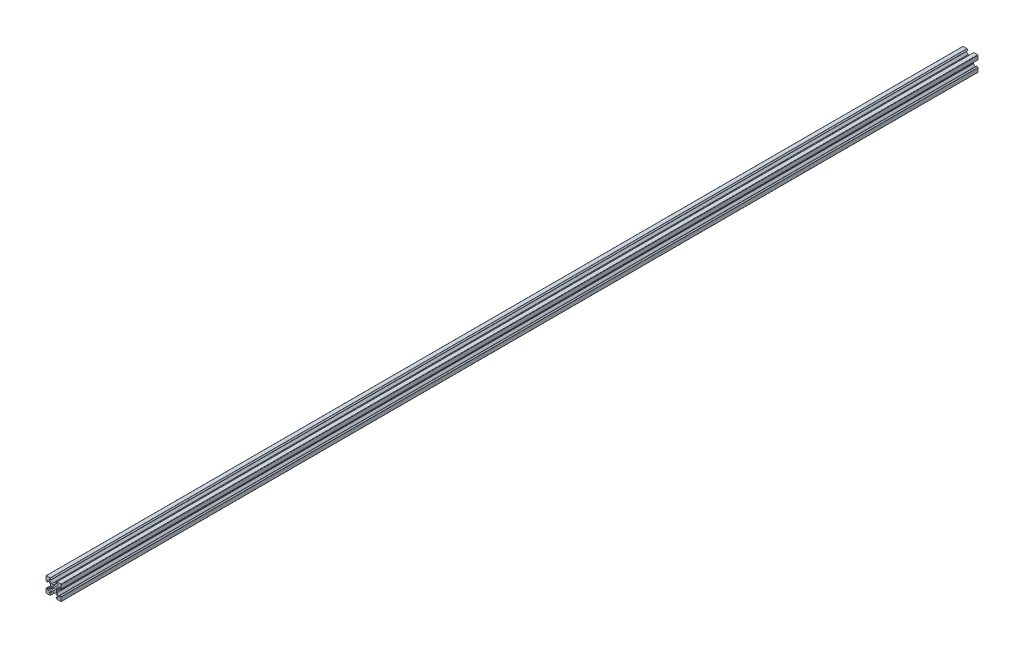
SolidWorks part; units mm, degrees
ref_plane "Front Plane" through (0, 0, 0) normal (0, 0, 1) x (1, 0, 0)
ref_plane "Top Plane" through (0, 0, 0) normal (0, 1, 0) x (1, 0, 0)
ref_plane "Right Plane" through (0, 0, 0) normal (1, 0, 0) x (0, 0, -1)
sketch "Model" plane through (0, 0, 0) normal (0, 0, 1) x (1, 0, 0)
  line L0 (1975.9541, 1652.1362) -> (1976.9672, 1652.4076)
  line L1 (1973.0632, 1648.5036) -> (1973.3346, 1649.5167)
  line L2 (1968.2453, 1649.5167) -> (1968.5168, 1648.5036)
  line L3 (1964.6128, 1652.4076) -> (1965.6258, 1652.1362)
  line L4 (1965.6258, 1657.2255) -> (1964.6128, 1656.954)
  line L5 (1968.5168, 1660.858) -> (1968.2453, 1659.845)
  line L6 (1973.3346, 1659.845) -> (1973.0632, 1660.858)
  line L7 (1976.9672, 1656.954) -> (1975.9541, 1657.2255)
  line L8 (2004.5828, 1634.6808) -> (1993.79, 1634.6808)
  line L9 (2005.6258, 1652.1362) -> (2004.6128, 1652.4076)
  line L10 (2008.5168, 1648.5036) -> (2008.2453, 1649.5167)
  line L11 (2013.3346, 1649.5167) -> (2013.0632, 1648.5036)
  line L12 (2016.9672, 1652.4076) -> (2015.9541, 1652.1362)
  line L13 (2015.9541, 1657.2255) -> (2016.9672, 1656.954)
  line L14 (2013.0632, 1660.858) -> (2013.3346, 1659.845)
  line L15 (2008.2453, 1659.845) -> (2008.5168, 1660.858)
  line L16 (2004.6128, 1656.954) -> (2005.6258, 1657.2255)
  line L17 (1980.5086, 1646.6346) -> (1986.1807, 1640.6604)
  line L18 (1995.3992, 1640.6604) -> (2001.0713, 1646.6346)
  line L19 (2001.0713, 1662.727) -> (1995.3992, 1668.7012)
  line L20 (1986.1807, 1668.7012) -> (1980.5086, 1662.727)
  line L21 (1993.79, 1674.6808) -> (2004.5828, 1674.6808)
  line L22 (2004.5828, 1674.6808) -> (1976.9971, 1674.6808)
  line L23 (1976.6435, 1674.5344) -> (1974.9364, 1672.8273)
  line L24 (1974.79, 1672.4737) -> (1974.79, 1670.8808)
  line L25 (1975.29, 1670.3808) -> (1976.29, 1670.3808)
  line L26 (1976.79, 1670.8808) -> (1976.79, 1671.7281)
  line L27 (1976.8778, 1671.9403) -> (1977.5305, 1672.593)
  line L28 (1977.7426, 1672.6808) -> (1982.5473, 1672.6808)
  line L29 (1983.9244, 1669.2304) -> (1978.8362, 1664.3995)
  line L30 (1962.7437, 1664.3995) -> (1957.6555, 1669.2304)
  line L31 (1959.0326, 1672.6808) -> (1963.8373, 1672.6808)
  line L32 (1964.0494, 1672.593) -> (1964.7021, 1671.9403)
  line L33 (1964.79, 1671.7281) -> (1964.79, 1670.8808)
  line L34 (1965.29, 1670.3808) -> (1966.29, 1670.3808)
  line L35 (1966.79, 1670.8808) -> (1966.79, 1672.4737)
  line L36 (1966.6435, 1672.8273) -> (1964.9364, 1674.5344)
  line L37 (1964.5828, 1674.6808) -> (1953.79, 1674.6808)
  line L38 (1950.79, 1671.6808) -> (1950.79, 1660.8879)
  line L39 (1950.9364, 1660.5344) -> (1952.6435, 1658.8273)
  line L40 (1952.9971, 1658.6808) -> (1954.59, 1658.6808)
  line L41 (1955.09, 1659.1808) -> (1955.09, 1660.1808)
  line L42 (1954.59, 1660.6808) -> (1953.7426, 1660.6808)
  line L43 (1953.5305, 1660.7687) -> (1952.8778, 1661.4214)
  line L44 (1952.79, 1661.6335) -> (1952.79, 1666.4382)
  line L45 (1956.2404, 1667.8153) -> (1961.0713, 1662.727)
  line L46 (1961.0713, 1646.6346) -> (1956.2404, 1641.5464)
  line L47 (1952.79, 1642.9235) -> (1952.79, 1647.7281)
  line L48 (1952.8778, 1647.9403) -> (1953.5305, 1648.593)
  line L49 (1953.7426, 1648.6808) -> (1954.59, 1648.6808)
  line L50 (1955.09, 1649.1808) -> (1955.09, 1650.1808)
  line L51 (1954.59, 1650.6808) -> (1952.9971, 1650.6808)
  line L52 (1952.6435, 1650.5344) -> (1950.9364, 1648.8273)
  line L53 (1950.79, 1648.4737) -> (1950.79, 1637.6808)
  line L54 (1953.79, 1634.6808) -> (1964.5828, 1634.6808)
  line L55 (1964.9364, 1634.8273) -> (1966.6435, 1636.5344)
  line L56 (1966.79, 1636.8879) -> (1966.79, 1638.4808)
  line L57 (1966.29, 1638.9808) -> (1965.29, 1638.9808)
  line L58 (1964.79, 1638.4808) -> (1964.79, 1637.6335)
  line L59 (1964.7021, 1637.4214) -> (1964.0494, 1636.7687)
  line L60 (1963.8373, 1636.6808) -> (1959.0326, 1636.6808)
  line L61 (1957.6555, 1640.1312) -> (1962.7437, 1644.9622)
  line L62 (1978.8362, 1644.9622) -> (1983.9244, 1640.1312)
  line L63 (1982.5473, 1636.6808) -> (1977.7426, 1636.6808)
  line L64 (1977.5305, 1636.7687) -> (1976.8778, 1637.4214)
  line L65 (1976.79, 1637.6335) -> (1976.79, 1638.4808)
  line L66 (1976.29, 1638.9808) -> (1975.29, 1638.9808)
  line L67 (1974.79, 1638.4808) -> (1974.79, 1636.8879)
  line L68 (1974.9364, 1636.5344) -> (1976.6435, 1634.8273)
  line L69 (1976.9971, 1634.6808) -> (2004.5828, 1634.6808)
  line L70 (2004.9364, 1634.8273) -> (2006.6435, 1636.5344)
  line L71 (2006.79, 1636.8879) -> (2006.79, 1638.4808)
  line L72 (2006.29, 1638.9808) -> (2005.29, 1638.9808)
  line L73 (2004.79, 1638.4808) -> (2004.79, 1637.6335)
  line L74 (2004.7021, 1637.4214) -> (2004.0494, 1636.7687)
  line L75 (2003.8373, 1636.6808) -> (1999.0326, 1636.6808)
  line L76 (1997.6555, 1640.1312) -> (2002.7437, 1644.9622)
  line L77 (2018.8362, 1644.9622) -> (2023.9244, 1640.1312)
  line L78 (2022.5473, 1636.6808) -> (2017.7426, 1636.6808)
  line L79 (2017.5305, 1636.7687) -> (2016.8778, 1637.4214)
  line L80 (2016.79, 1637.6335) -> (2016.79, 1638.4808)
  line L81 (2016.29, 1638.9808) -> (2015.29, 1638.9808)
  line L82 (2014.79, 1638.4808) -> (2014.79, 1636.8879)
  line L83 (2014.9364, 1636.5344) -> (2016.6435, 1634.8273)
  line L84 (2016.9971, 1634.6808) -> (2027.79, 1634.6808)
  line L85 (2030.79, 1637.6808) -> (2030.79, 1648.4737)
  line L86 (2030.6435, 1648.8273) -> (2028.9364, 1650.5344)
  line L87 (2028.5828, 1650.6808) -> (2026.99, 1650.6808)
  line L88 (2026.49, 1650.1808) -> (2026.49, 1649.1808)
  line L89 (2026.99, 1648.6808) -> (2027.8373, 1648.6808)
  line L90 (2028.0494, 1648.593) -> (2028.7021, 1647.9403)
  line L91 (2028.79, 1647.7281) -> (2028.79, 1642.9235)
  line L92 (2025.3395, 1641.5464) -> (2020.5086, 1646.6346)
  line L93 (2020.5086, 1662.727) -> (2025.3395, 1667.8153)
  line L94 (2028.79, 1666.4382) -> (2028.79, 1661.6335)
  line L95 (2028.7021, 1661.4214) -> (2028.0494, 1660.7687)
  line L96 (2027.8373, 1660.6808) -> (2026.99, 1660.6808)
  line L97 (2026.49, 1660.1808) -> (2026.49, 1659.1808)
  line L98 (2026.99, 1658.6808) -> (2028.5828, 1658.6808)
  line L99 (2028.9364, 1658.8273) -> (2030.6435, 1660.5344)
  line L100 (2030.79, 1660.8879) -> (2030.79, 1671.6808)
  line L101 (2027.79, 1674.6808) -> (2016.9971, 1674.6808)
  line L102 (2016.6435, 1674.5344) -> (2014.9364, 1672.8273)
  line L103 (2014.79, 1672.4737) -> (2014.79, 1670.8808)
  line L104 (2015.29, 1670.3808) -> (2016.29, 1670.3808)
  line L105 (2016.79, 1670.8808) -> (2016.79, 1671.7281)
  line L106 (2016.8778, 1671.9403) -> (2017.5305, 1672.593)
  line L107 (2017.7426, 1672.6808) -> (2022.5473, 1672.6808)
  line L108 (2023.9244, 1669.2304) -> (2018.8362, 1664.3995)
  line L109 (2002.7437, 1664.3995) -> (1997.6555, 1669.2304)
  line L110 (1999.0326, 1672.6808) -> (2003.8373, 1672.6808)
  line L111 (2004.0494, 1672.593) -> (2004.7021, 1671.9403)
  line L112 (2004.79, 1671.7281) -> (2004.79, 1670.8808)
  line L113 (2005.29, 1670.3808) -> (2006.29, 1670.3808)
  line L114 (2006.79, 1670.8808) -> (2006.79, 1672.4737)
  line L115 (2006.6435, 1672.8273) -> (2004.9364, 1674.5344)
  line L116 (2218.2015, 1641.0792) -> (2218.2015, 1642.0932)
  line L117 (2217.6945, 1642.6002) -> (2216.0793, 1642.6002)
  line L118 (2215.7208, 1642.4517) -> (2213.9898, 1640.7207)
  line L119 (2213.8413, 1640.3622) -> (2213.8413, 1629.4182)
  line L120 (2216.8833, 1626.3762) -> (2227.8273, 1626.3762)
  line L121 (2228.1858, 1626.5247) -> (2229.9168, 1628.2557)
  line L122 (2230.0653, 1628.6142) -> (2230.0653, 1630.2294)
  line L123 (2229.5583, 1630.7364) -> (2228.5443, 1630.7364)
  line L124 (2228.0373, 1630.2294) -> (2228.0373, 1629.3702)
  line L125 (2227.9482, 1629.1551) -> (2227.2864, 1628.4933)
  line L126 (2227.0713, 1628.4042) -> (2221.0306, 1628.4042)
  line L127 (2219.9554, 1631.0982) -> (2225.9624, 1636.8015)
  line L128 (2242.2802, 1636.8015) -> (2248.2872, 1631.0982)
  line L129 (2247.212, 1628.4042) -> (2241.1713, 1628.4042)
  line L130 (2240.9562, 1628.4933) -> (2240.2944, 1629.1551)
  line L131 (2240.2053, 1629.3702) -> (2240.2053, 1630.2294)
  line L132 (2239.6983, 1630.7364) -> (2238.6843, 1630.7364)
  line L133 (2238.1773, 1630.2294) -> (2238.1773, 1628.6142)
  line L134 (2238.3258, 1628.2557) -> (2240.0568, 1626.5247)
  line L135 (2240.4153, 1626.3762) -> (2251.3593, 1626.3762)
  line L136 (2254.4013, 1629.4182) -> (2254.4013, 1640.3622)
  line L137 (2254.2528, 1640.7207) -> (2252.5218, 1642.4517)
  line L138 (2252.1633, 1642.6002) -> (2250.5481, 1642.6002)
  line L139 (2250.0411, 1642.0932) -> (2250.0411, 1641.0792)
  line L140 (2250.5481, 1640.5722) -> (2251.4073, 1640.5722)
  line L141 (2251.6224, 1640.4831) -> (2252.2842, 1639.8213)
  line L142 (2252.3733, 1639.6062) -> (2252.3733, 1633.5655)
  line L143 (2249.6793, 1632.4903) -> (2243.976, 1638.4973)
  line L144 (2243.976, 1654.8151) -> (2249.6793, 1660.8221)
  line L145 (2252.3733, 1659.7469) -> (2252.3733, 1653.7062)
  line L146 (2252.2842, 1653.4911) -> (2251.6224, 1652.8293)
  line L147 (2251.4073, 1652.7402) -> (2250.5481, 1652.7402)
  line L148 (2250.0411, 1652.2332) -> (2250.0411, 1651.2192)
  line L149 (2250.5481, 1650.7122) -> (2252.1633, 1650.7122)
  line L150 (2252.5218, 1650.8607) -> (2254.2528, 1652.5917)
  line L151 (2254.4013, 1652.9502) -> (2254.4013, 1663.8942)
  line L152 (2251.3593, 1666.9362) -> (2240.4153, 1666.9362)
  line L153 (2240.0568, 1666.7877) -> (2238.3258, 1665.0567)
  line L154 (2238.1773, 1664.6982) -> (2238.1773, 1663.083)
  line L155 (2238.6843, 1662.576) -> (2239.6983, 1662.576)
  line L156 (2240.2053, 1663.083) -> (2240.2053, 1663.9422)
  line L157 (2240.2944, 1664.1573) -> (2240.9562, 1664.8191)
  line L158 (2241.1713, 1664.9082) -> (2247.212, 1664.9082)
  line L159 (2248.2872, 1662.2142) -> (2242.2802, 1656.5109)
  line L160 (2225.9624, 1656.5109) -> (2219.9554, 1662.2142)
  line L161 (2221.0306, 1664.9082) -> (2227.0713, 1664.9082)
  line L162 (2227.2864, 1664.8191) -> (2227.9482, 1664.1573)
  line L163 (2228.0373, 1663.9422) -> (2228.0373, 1663.083)
  line L164 (2228.5443, 1662.576) -> (2229.5583, 1662.576)
  line L165 (2230.0653, 1663.083) -> (2230.0653, 1664.6982)
  line L166 (2229.9168, 1665.0567) -> (2228.1858, 1666.7877)
  line L167 (2227.8273, 1666.9362) -> (2216.8833, 1666.9362)
  line L168 (2213.8413, 1663.8942) -> (2213.8413, 1652.9502)
  line L169 (2213.9898, 1652.5917) -> (2215.7208, 1650.8607)
  line L170 (2216.0793, 1650.7122) -> (2217.6945, 1650.7122)
  line L171 (2218.2015, 1651.2192) -> (2218.2015, 1652.2332)
  line L172 (2217.6945, 1652.7402) -> (2216.8353, 1652.7402)
  line L173 (2216.6202, 1652.8293) -> (2215.9584, 1653.4911)
  line L174 (2215.8693, 1653.7062) -> (2215.8693, 1659.7469)
  line L175 (2218.5633, 1660.8221) -> (2224.2666, 1654.8151)
  line L176 (2224.2666, 1638.4973) -> (2218.5633, 1632.4903)
  line L177 (2215.8693, 1633.5655) -> (2215.8693, 1639.6062)
  line L178 (2215.9584, 1639.8213) -> (2216.6202, 1640.4831)
  line L179 (2216.8353, 1640.5722) -> (2217.6945, 1640.5722)
  line L180 (2228.8737, 1644.1116) -> (2227.8607, 1644.383)
  line L181 (2231.7647, 1640.479) -> (2231.4932, 1641.4921)
  line L182 (2236.5825, 1641.4921) -> (2236.3111, 1640.479)
  line L183 (2240.2151, 1644.383) -> (2239.202, 1644.1116)
  line L184 (2239.202, 1649.2008) -> (2240.2151, 1648.9294)
  line L185 (2236.3111, 1652.8334) -> (2236.5825, 1651.8203)
  line L186 (2231.4932, 1651.8203) -> (2231.7647, 1652.8334)
  line L187 (2227.8607, 1648.9294) -> (2228.8737, 1649.2008)
  line L188 (2260.9191, 1499.2537) -> (2259.5984, 1499.2537)
  line L189 (2259.3484, 1499.0037) -> (2259.3484, 1497.1537)
  line L190 (2258.9216, 1496.9769) -> (2257.7363, 1498.1623)
  line L191 (2257.6484, 1498.3744) -> (2257.6484, 1503.3037)
  line L192 (2258.1484, 1503.8037) -> (2263.0777, 1503.8037)
  line L193 (2263.2898, 1503.7158) -> (2264.4752, 1502.5305)
  line L194 (2264.2984, 1502.1037) -> (2262.4484, 1502.1037)
  line L195 (2262.1984, 1501.8537) -> (2262.1984, 1500.533)
  line L196 (2262.2716, 1500.3562) -> (2264.751, 1497.8769)
  line L197 (2264.9278, 1497.8037) -> (2267.1874, 1497.8037)
  line L198 (2268.1094, 1497.8037) -> (2270.3691, 1497.8037)
  line L199 (2270.5459, 1497.8769) -> (2273.0252, 1500.3562)
  line L200 (2273.0984, 1500.533) -> (2273.0984, 1501.8537)
  line L201 (2272.8484, 1502.1037) -> (2270.9984, 1502.1037)
  line L202 (2270.8216, 1502.5305) -> (2272.007, 1503.7158)
  line L203 (2272.2191, 1503.8037) -> (2283.0777, 1503.8037)
  line L204 (2283.2898, 1503.7158) -> (2284.4752, 1502.5305)
  line L205 (2284.2984, 1502.1037) -> (2282.4484, 1502.1037)
  line L206 (2282.1984, 1501.8537) -> (2282.1984, 1500.533)
  line L207 (2282.2716, 1500.3562) -> (2284.751, 1497.8769)
  line L208 (2284.9278, 1497.8037) -> (2287.1874, 1497.8037)
  line L209 (2288.1094, 1497.8037) -> (2290.3691, 1497.8037)
  line L210 (2290.5459, 1497.8769) -> (2293.0252, 1500.3562)
  line L211 (2293.0984, 1500.533) -> (2293.0984, 1501.8537)
  line L212 (2292.8484, 1502.1037) -> (2290.9984, 1502.1037)
  line L213 (2290.8216, 1502.5305) -> (2292.007, 1503.7158)
  line L214 (2292.2191, 1503.8037) -> (2297.1484, 1503.8037)
  line L215 (2297.6484, 1503.3037) -> (2297.6484, 1498.3744)
  line L216 (2297.5606, 1498.1623) -> (2296.3752, 1496.9769)
  line L217 (2295.9484, 1497.1537) -> (2295.9484, 1499.0037)
  line L218 (2295.6984, 1499.2537) -> (2294.3778, 1499.2537)
  line L219 (2294.201, 1499.1805) -> (2291.7363, 1496.7158)
  line L220 (2291.6484, 1496.5037) -> (2291.6484, 1495.6037)
  line L221 (2291.3484, 1495.3037) -> (2290.4485, 1495.3037)
  line L222 (2290.2363, 1495.2158) -> (2289.8912, 1494.8707)
  line L223 (2289.8912, 1492.7366) -> (2290.2363, 1492.3916)
  line L224 (2290.4485, 1492.3037) -> (2291.3484, 1492.3037)
  line L225 (2291.6484, 1492.0037) -> (2291.6484, 1491.1037)
  line L226 (2291.7363, 1490.8916) -> (2294.201, 1488.4269)
  line L227 (2294.3778, 1488.3537) -> (2295.6984, 1488.3537)
  line L228 (2295.9484, 1488.6037) -> (2295.9484, 1490.4537)
  line L229 (2296.3752, 1490.6305) -> (2297.5606, 1489.4451)
  line L230 (2297.6484, 1489.233) -> (2297.6484, 1484.3037)
  line L231 (2297.1484, 1483.8037) -> (2292.2191, 1483.8037)
  line L232 (2292.007, 1483.8916) -> (2290.8216, 1485.0769)
  line L233 (2290.9984, 1485.5037) -> (2292.8484, 1485.5037)
  line L234 (2293.0984, 1485.7537) -> (2293.0984, 1487.0744)
  line L235 (2293.0252, 1487.2511) -> (2290.5459, 1489.7305)
  line L236 (2290.3691, 1489.8037) -> (2288.1094, 1489.8037)
  line L237 (2287.1874, 1489.8037) -> (2284.9278, 1489.8037)
  line L238 (2284.751, 1489.7305) -> (2282.2716, 1487.2511)
  line L239 (2282.1984, 1487.0744) -> (2282.1984, 1485.7537)
  line L240 (2282.4484, 1485.5037) -> (2284.2984, 1485.5037)
  line L241 (2284.4752, 1485.0769) -> (2283.2898, 1483.8916)
  line L242 (2283.0777, 1483.8037) -> (2272.2191, 1483.8037)
  line L243 (2272.007, 1483.8916) -> (2270.8216, 1485.0769)
  line L244 (2270.9984, 1485.5037) -> (2272.8484, 1485.5037)
  line L245 (2273.0984, 1485.7537) -> (2273.0984, 1487.0744)
  line L246 (2273.0252, 1487.2511) -> (2270.5459, 1489.7305)
  line L247 (2270.3691, 1489.8037) -> (2268.1094, 1489.8037)
  line L248 (2267.1874, 1489.8037) -> (2264.9278, 1489.8037)
  line L249 (2264.751, 1489.7305) -> (2262.2716, 1487.2511)
  line L250 (2262.1984, 1487.0744) -> (2262.1984, 1485.7537)
  line L251 (2262.4484, 1485.5037) -> (2264.2984, 1485.5037)
  line L252 (2264.4752, 1485.0769) -> (2263.2898, 1483.8916)
  line L253 (2263.0777, 1483.8037) -> (2258.1484, 1483.8037)
  line L254 (2257.6484, 1484.3037) -> (2257.6484, 1489.233)
  line L255 (2257.7363, 1489.4451) -> (2258.9216, 1490.6305)
  line L256 (2259.3484, 1490.4537) -> (2259.3484, 1488.6037)
  line L257 (2259.5984, 1488.3537) -> (2260.9191, 1488.3537)
  line L258 (2261.0959, 1488.4269) -> (2263.5606, 1490.8916)
  line L259 (2263.6484, 1491.1037) -> (2263.6484, 1492.0037)
  line L260 (2263.9484, 1492.3037) -> (2264.8484, 1492.3037)
  line L261 (2265.0605, 1492.3916) -> (2265.4056, 1492.7366)
  line L262 (2265.4056, 1494.8707) -> (2265.0605, 1495.2158)
  line L263 (2264.8484, 1495.3037) -> (2263.9484, 1495.3037)
  line L264 (2263.6484, 1495.6037) -> (2263.6484, 1496.5037)
  line L265 (2263.5606, 1496.7158) -> (2261.0959, 1499.1805)
  line L266 (2013.2312, 1378.5004) -> (2014.1312, 1378.5004)
  line L267 (2014.3433, 1378.5883) -> (2014.6884, 1378.9333)
  line L268 (2014.6884, 1381.0674) -> (2014.3433, 1381.4125)
  line L269 (2014.1312, 1381.5004) -> (2013.2312, 1381.5004)
  line L270 (2012.9312, 1381.8004) -> (2012.9312, 1382.7004)
  line L271 (2012.8433, 1382.9125) -> (2010.3787, 1385.3772)
  line L272 (2010.2019, 1385.4504) -> (2008.8812, 1385.4504)
  line L273 (2008.6312, 1385.2004) -> (2008.6312, 1383.3504)
  line L274 (2008.2044, 1383.1736) -> (2007.0191, 1384.359)
  line L275 (2006.9312, 1384.5711) -> (2006.9312, 1389.5004)
  line L276 (2007.4312, 1390.0004) -> (2012.3605, 1390.0004)
  line L277 (2012.5726, 1389.9125) -> (2013.758, 1388.7272)
  line L278 (2013.5812, 1388.3004) -> (2011.7312, 1388.3004)
  line L279 (2011.4812, 1388.0504) -> (2011.4812, 1386.7297)
  line L280 (2011.5544, 1386.5529) -> (2014.0338, 1384.0736)
  line L281 (2014.2105, 1384.0004) -> (2016.4702, 1384.0004)
  line L282 (2017.3922, 1384.0004) -> (2019.6519, 1384.0004)
  line L283 (2019.8287, 1384.0736) -> (2022.308, 1386.5529)
  line L284 (2022.3812, 1386.7297) -> (2022.3812, 1388.0504)
  line L285 (2022.1312, 1388.3004) -> (2020.2812, 1388.3004)
  line L286 (2020.1044, 1388.7272) -> (2021.2898, 1389.9125)
  line L287 (2021.5019, 1390.0004) -> (2026.4312, 1390.0004)
  line L288 (2026.9312, 1389.5004) -> (2026.9312, 1384.5711)
  line L289 (2026.8433, 1384.359) -> (2025.658, 1383.1736)
  line L290 (2025.2312, 1383.3504) -> (2025.2312, 1385.2004)
  line L291 (2024.9812, 1385.4504) -> (2023.6605, 1385.4504)
  line L292 (2023.4838, 1385.3772) -> (2021.0044, 1382.8978)
  line L293 (2020.9312, 1382.7211) -> (2020.9312, 1380.4614)
  line L294 (2020.9312, 1379.5394) -> (2020.9312, 1377.2797)
  line L295 (2021.0044, 1377.1029) -> (2023.4838, 1374.6236)
  line L296 (2023.6605, 1374.5504) -> (2024.9812, 1374.5504)
  line L297 (2025.2312, 1374.8004) -> (2025.2312, 1376.6504)
  line L298 (2025.658, 1376.8272) -> (2026.8433, 1375.6418)
  line L299 (2026.9312, 1375.4297) -> (2026.9312, 1370.5004)
  line L300 (2026.4312, 1370.0004) -> (2021.5019, 1370.0004)
  line L301 (2021.2898, 1370.0883) -> (2020.1044, 1371.2736)
  line L302 (2020.2812, 1371.7004) -> (2022.1312, 1371.7004)
  line L303 (2022.3812, 1371.9504) -> (2022.3812, 1373.2711)
  line L304 (2022.308, 1373.4478) -> (2019.8287, 1375.9272)
  line L305 (2019.6519, 1376.0004) -> (2017.3922, 1376.0004)
  line L306 (2016.4702, 1376.0004) -> (2014.2105, 1376.0004)
  line L307 (2014.0338, 1375.9272) -> (2011.5544, 1373.4478)
  line L308 (2011.4812, 1373.2711) -> (2011.4812, 1371.9504)
  line L309 (2011.7312, 1371.7004) -> (2013.5812, 1371.7004)
  line L310 (2013.758, 1371.2736) -> (2012.5726, 1370.0883)
  line L311 (2012.3605, 1370.0004) -> (2007.4312, 1370.0004)
  line L312 (2006.9312, 1370.5004) -> (2006.9312, 1375.4297)
  line L313 (2007.0191, 1375.6418) -> (2008.2044, 1376.8272)
  line L314 (2008.6312, 1376.6504) -> (2008.6312, 1374.8004)
  line L315 (2008.8812, 1374.5504) -> (2010.2019, 1374.5504)
  line L316 (2010.3787, 1374.6236) -> (2012.8433, 1377.0883)
  line L317 (2012.9312, 1377.3004) -> (2012.9312, 1378.2004)
  line L318 (2022.212, 1489.807) -> (2016.4201, 1489.807)
  line L319 (2015.5038, 1489.807) -> (2009.712, 1489.807)
  line L320 (2006.712, 1492.807) -> (2006.712, 1496.5112)
  line L321 (2007.012, 1496.8112) -> (2011.612, 1496.8112)
  line L322 (2011.912, 1497.1112) -> (2011.912, 1500.5112)
  line L323 (2011.612, 1500.8112) -> (2004.7979, 1500.8112)
  line L324 (2003.876, 1500.8112) -> (1996.262, 1500.8112)
  line L325 (1995.962, 1500.5112) -> (1995.962, 1495.3819)
  line L326 (1996.0498, 1495.1698) -> (1997.2352, 1493.9844)
  line L327 (1997.662, 1494.1612) -> (1997.662, 1496.0112)
  line L328 (1997.912, 1496.2612) -> (1999.2326, 1496.2612)
  line L329 (1999.4094, 1496.188) -> (2001.8887, 1493.7086)
  line L330 (2001.962, 1493.5319) -> (2001.962, 1491.2722)
  line L331 (2001.962, 1490.3502) -> (2001.962, 1488.0905)
  line L332 (2001.8887, 1487.9137) -> (1999.4094, 1485.4344)
  line L333 (1999.2326, 1485.3612) -> (1997.912, 1485.3612)
  line L334 (1997.662, 1485.6112) -> (1997.662, 1487.4612)
  line L335 (1997.2352, 1487.638) -> (1996.0498, 1486.4526)
  line L336 (1995.962, 1486.2405) -> (1995.962, 1481.1112)
  line L337 (1996.262, 1480.8112) -> (2001.3913, 1480.8112)
  line L338 (2001.6034, 1480.8991) -> (2002.7887, 1482.0844)
  line L339 (2002.612, 1482.5112) -> (2000.762, 1482.5112)
  line L340 (2000.512, 1482.7612) -> (2000.512, 1484.0819)
  line L341 (2000.5852, 1484.2587) -> (2003.0645, 1486.738)
  line L342 (2003.2413, 1486.8112) -> (2005.501, 1486.8112)
  line L343 (2006.4229, 1486.8112) -> (2008.6826, 1486.8112)
  line L344 (2008.8594, 1486.738) -> (2011.3387, 1484.2587)
  line L345 (2011.412, 1484.0819) -> (2011.412, 1482.7612)
  line L346 (2011.162, 1482.5112) -> (2009.312, 1482.5112)
  line L347 (2009.1352, 1482.0844) -> (2010.3205, 1480.8991)
  line L348 (2010.5327, 1480.8112) -> (2015.501, 1480.8112)
  line L349 (2016.4229, 1480.8112) -> (2021.3913, 1480.8112)
  line L350 (2021.6034, 1480.8991) -> (2022.7887, 1482.0844)
  line L351 (2022.612, 1482.5112) -> (2020.762, 1482.5112)
  line L352 (2020.512, 1482.7612) -> (2020.512, 1484.0819)
  line L353 (2020.5852, 1484.2587) -> (2023.0645, 1486.738)
  line L354 (2023.2413, 1486.8112) -> (2025.501, 1486.8112)
  line L355 (2026.4229, 1486.8112) -> (2028.6826, 1486.8112)
  line L356 (2028.8594, 1486.738) -> (2031.3387, 1484.2587)
  line L357 (2031.412, 1484.0819) -> (2031.412, 1482.7612)
  line L358 (2031.162, 1482.5112) -> (2029.312, 1482.5112)
  line L359 (2029.1352, 1482.0844) -> (2030.3205, 1480.8991)
  line L360 (2030.5327, 1480.8112) -> (2035.662, 1480.8112)
  line L361 (2035.962, 1481.1112) -> (2035.962, 1486.2405)
  line L362 (2035.8741, 1486.4526) -> (2034.6887, 1487.638)
  line L363 (2034.262, 1487.4612) -> (2034.262, 1485.6112)
  line L364 (2034.012, 1485.3612) -> (2032.6913, 1485.3612)
  line L365 (2032.5145, 1485.4344) -> (2030.0352, 1487.9137)
  line L366 (2029.962, 1488.0905) -> (2029.962, 1490.3502)
  line L367 (2029.962, 1491.2722) -> (2029.962, 1493.5319)
  line L368 (2030.0352, 1493.7086) -> (2032.5145, 1496.188)
  line L369 (2032.6913, 1496.2612) -> (2034.012, 1496.2612)
  line L370 (2034.262, 1496.0112) -> (2034.262, 1494.1612)
  line L371 (2034.6887, 1493.9844) -> (2035.8741, 1495.1698)
  line L372 (2035.962, 1495.3819) -> (2035.962, 1500.5112)
  line L373 (2035.662, 1500.8112) -> (2028.0479, 1500.8112)
  line L374 (2027.126, 1500.8112) -> (2020.312, 1500.8112)
  line L375 (2020.012, 1500.5112) -> (2020.012, 1497.1112)
  line L376 (2020.312, 1496.8112) -> (2024.912, 1496.8112)
  line L377 (2025.212, 1496.5112) -> (2025.212, 1492.807)
  arc A0 (1977.3429, 1652.084) -> (1976.9672, 1652.4076) centre (1977.0448, 1652.1178) ccw
  arc A1 (1977.215, 1651.1353) -> (1977.3429, 1652.084) centre (1954.49, 1654.6808) ccw
  arc A2 (1977.215, 1651.1353) -> (1977.3, 1648.529) centre (1984.1314, 1650.0562) ccw
  arc A3 (1976.9418, 1648.1708) -> (1977.3, 1648.529) centre (1977.0072, 1648.4635) ccw
  arc A4 (1976.9418, 1648.1708) -> (1974.3355, 1648.2557) centre (1975.4145, 1641.3394) ccw
  arc A5 (1973.3868, 1648.1279) -> (1974.3355, 1648.2557) centre (1970.79, 1670.9808) ccw
  arc A6 (1973.0632, 1648.5036) -> (1973.3868, 1648.1279) centre (1973.3529, 1648.426) ccw
  arc A7 (1973.3346, 1649.5167) -> (1971.5503, 1651.3669) centre (1971.8857, 1649.9049) ccw
  arc A8 (1970.0296, 1651.3669) -> (1971.5503, 1651.3669) centre (1970.79, 1654.6808) ccw
  arc A9 (1970.0296, 1651.3669) -> (1968.2453, 1649.5167) centre (1969.6942, 1649.9049) ccw
  arc A10 (1968.1931, 1648.1279) -> (1968.5168, 1648.5036) centre (1968.227, 1648.426) ccw
  arc A11 (1967.2444, 1648.2557) -> (1968.1931, 1648.1279) centre (1970.79, 1670.9808) ccw
  arc A12 (1967.2444, 1648.2557) -> (1964.6381, 1648.1708) centre (1966.1654, 1641.3394) ccw
  arc A13 (1964.2799, 1648.529) -> (1964.6381, 1648.1708) centre (1964.5727, 1648.4635) ccw
  arc A14 (1964.2799, 1648.529) -> (1964.3649, 1651.1353) centre (1957.4485, 1650.0562) ccw
  arc A15 (1964.237, 1652.084) -> (1964.3649, 1651.1353) centre (1987.09, 1654.6808) ccw
  arc A16 (1964.6128, 1652.4076) -> (1964.237, 1652.084) centre (1964.5351, 1652.1178) ccw
  arc A17 (1965.6258, 1652.1362) -> (1967.4761, 1653.9205) centre (1966.014, 1653.5851) ccw
  arc A18 (1967.4761, 1655.4411) -> (1967.4761, 1653.9205) centre (1970.79, 1654.6808) ccw
  arc A19 (1967.4761, 1655.4411) -> (1965.6258, 1657.2255) centre (1966.014, 1655.7766) ccw
  arc A20 (1964.237, 1657.2777) -> (1964.6128, 1656.954) centre (1964.5351, 1657.2438) ccw
  arc A21 (1964.3649, 1658.2263) -> (1964.237, 1657.2777) centre (1987.09, 1654.6808) ccw
  arc A22 (1964.3649, 1658.2263) -> (1964.2799, 1660.8326) centre (1957.4485, 1659.3054) ccw
  arc A23 (1964.6381, 1661.1909) -> (1964.2799, 1660.8326) centre (1964.5727, 1660.8981) ccw
  arc A24 (1964.6381, 1661.1909) -> (1967.2444, 1661.1059) centre (1966.1654, 1668.0222) ccw
  arc A25 (1968.1931, 1661.2338) -> (1967.2444, 1661.1059) centre (1970.79, 1638.3808) ccw
  arc A26 (1968.5168, 1660.858) -> (1968.1931, 1661.2338) centre (1968.227, 1660.9357) ccw
  arc A27 (1968.2453, 1659.845) -> (1970.0296, 1657.9947) centre (1969.6942, 1659.4567) ccw
  arc A28 (1971.5503, 1657.9947) -> (1970.0296, 1657.9947) centre (1970.79, 1654.6808) ccw
  arc A29 (1971.5503, 1657.9947) -> (1973.3346, 1659.845) centre (1971.8857, 1659.4567) ccw
  arc A30 (1973.3868, 1661.2338) -> (1973.0632, 1660.858) centre (1973.3529, 1660.9357) ccw
  arc A31 (1974.3355, 1661.1059) -> (1973.3868, 1661.2338) centre (1970.79, 1638.3808) ccw
  arc A32 (1974.3355, 1661.1059) -> (1976.9418, 1661.1909) centre (1975.4145, 1668.0222) ccw
  arc A33 (1977.3, 1660.8326) -> (1976.9418, 1661.1909) centre (1977.0072, 1660.8981) ccw
  arc A34 (1977.3, 1660.8326) -> (1977.215, 1658.2263) centre (1984.1314, 1659.3054) ccw
  arc A35 (1977.3429, 1657.2777) -> (1977.215, 1658.2263) centre (1954.49, 1654.6808) ccw
  arc A36 (1976.9672, 1656.954) -> (1977.3429, 1657.2777) centre (1977.0448, 1657.2438) ccw
  arc A37 (1975.9541, 1657.2255) -> (1974.1039, 1655.4411) centre (1975.5659, 1655.7766) ccw
  arc A38 (1974.1039, 1653.9205) -> (1974.1039, 1655.4411) centre (1970.79, 1654.6808) ccw
  arc A39 (1974.1039, 1653.9205) -> (1975.9541, 1652.1362) centre (1975.5659, 1653.5851) ccw
  arc A40 (2004.6128, 1652.4076) -> (2004.237, 1652.084) centre (2004.5351, 1652.1178) ccw
  arc A41 (2004.237, 1652.084) -> (2004.3649, 1651.1353) centre (2027.09, 1654.6808) ccw
  arc A42 (2004.2799, 1648.529) -> (2004.3649, 1651.1353) centre (1997.4485, 1650.0562) ccw
  arc A43 (2004.2799, 1648.529) -> (2004.6381, 1648.1708) centre (2004.5727, 1648.4635) ccw
  arc A44 (2007.2444, 1648.2557) -> (2004.6381, 1648.1708) centre (2006.1654, 1641.3394) ccw
  arc A45 (2007.2444, 1648.2557) -> (2008.1931, 1648.1279) centre (2010.79, 1670.9808) ccw
  arc A46 (2008.1931, 1648.1279) -> (2008.5168, 1648.5036) centre (2008.227, 1648.426) ccw
  arc A47 (2010.0296, 1651.3669) -> (2008.2453, 1649.5167) centre (2009.6942, 1649.9049) ccw
  arc A48 (2010.0296, 1651.3669) -> (2011.5503, 1651.3669) centre (2010.79, 1654.6808) ccw
  arc A49 (2013.3346, 1649.5167) -> (2011.5503, 1651.3669) centre (2011.8857, 1649.9049) ccw
  arc A50 (2013.0632, 1648.5036) -> (2013.3868, 1648.1279) centre (2013.3529, 1648.426) ccw
  arc A51 (2013.3868, 1648.1279) -> (2014.3355, 1648.2557) centre (2010.79, 1670.9808) ccw
  arc A52 (2016.9418, 1648.1708) -> (2014.3355, 1648.2557) centre (2015.4145, 1641.3394) ccw
  arc A53 (2016.9418, 1648.1708) -> (2017.3, 1648.529) centre (2017.0072, 1648.4635) ccw
  arc A54 (2017.215, 1651.1353) -> (2017.3, 1648.529) centre (2024.1314, 1650.0562) ccw
  arc A55 (2017.215, 1651.1353) -> (2017.3429, 1652.084) centre (1994.49, 1654.6808) ccw
  arc A56 (2017.3429, 1652.084) -> (2016.9672, 1652.4076) centre (2017.0448, 1652.1178) ccw
  arc A57 (2014.1039, 1653.9205) -> (2015.9541, 1652.1362) centre (2015.5659, 1653.5851) ccw
  arc A58 (2014.1039, 1653.9205) -> (2014.1039, 1655.4411) centre (2010.79, 1654.6808) ccw
  arc A59 (2015.9541, 1657.2255) -> (2014.1039, 1655.4411) centre (2015.5659, 1655.7766) ccw
  arc A60 (2016.9672, 1656.954) -> (2017.3429, 1657.2777) centre (2017.0448, 1657.2438) ccw
  arc A61 (2017.3429, 1657.2777) -> (2017.215, 1658.2263) centre (1994.49, 1654.6808) ccw
  arc A62 (2017.3, 1660.8326) -> (2017.215, 1658.2263) centre (2024.1314, 1659.3054) ccw
  arc A63 (2017.3, 1660.8326) -> (2016.9418, 1661.1909) centre (2017.0072, 1660.8981) ccw
  arc A64 (2014.3355, 1661.1059) -> (2016.9418, 1661.1909) centre (2015.4145, 1668.0222) ccw
  arc A65 (2014.3355, 1661.1059) -> (2013.3868, 1661.2338) centre (2010.79, 1638.3808) ccw
  arc A66 (2013.3868, 1661.2338) -> (2013.0632, 1660.858) centre (2013.3529, 1660.9357) ccw
  arc A67 (2011.5503, 1657.9947) -> (2013.3346, 1659.845) centre (2011.8857, 1659.4567) ccw
  arc A68 (2011.5503, 1657.9947) -> (2010.0296, 1657.9947) centre (2010.79, 1654.6808) ccw
  arc A69 (2008.2453, 1659.845) -> (2010.0296, 1657.9947) centre (2009.6942, 1659.4567) ccw
  arc A70 (2008.5168, 1660.858) -> (2008.1931, 1661.2338) centre (2008.227, 1660.9357) ccw
  arc A71 (2008.1931, 1661.2338) -> (2007.2444, 1661.1059) centre (2010.79, 1638.3808) ccw
  arc A72 (2004.6381, 1661.1909) -> (2007.2444, 1661.1059) centre (2006.1654, 1668.0222) ccw
  arc A73 (2004.6381, 1661.1909) -> (2004.2799, 1660.8326) centre (2004.5727, 1660.8981) ccw
  arc A74 (2004.3649, 1658.2263) -> (2004.2799, 1660.8326) centre (1997.4485, 1659.3054) ccw
  arc A75 (2004.3649, 1658.2263) -> (2004.237, 1657.2777) centre (2027.09, 1654.6808) ccw
  arc A76 (2004.237, 1657.2777) -> (2004.6128, 1656.954) centre (2004.5351, 1657.2438) ccw
  arc A77 (2007.4761, 1655.4411) -> (2005.6258, 1657.2255) centre (2006.014, 1655.7766) ccw
  arc A78 (2007.4761, 1655.4411) -> (2007.4761, 1653.9205) centre (2010.79, 1654.6808) ccw
  arc A79 (2005.6258, 1652.1362) -> (2007.4761, 1653.9205) centre (2006.014, 1653.5851) ccw
  arc A80 (1979.1939, 1650.8445) -> (1979.1939, 1658.5171) centre (1954.49, 1654.6808) ccw
  arc A81 (1979.1939, 1650.8445) -> (1980.5086, 1646.6346) centre (1984.1346, 1650.0773) ccw
  arc A82 (1986.1807, 1640.6604) -> (1995.3992, 1640.6604) centre (1990.79, 1645.0366) ccw
  arc A83 (2001.0713, 1646.6346) -> (2002.3861, 1650.8445) centre (1997.4453, 1650.0773) ccw
  arc A84 (2002.3861, 1658.5171) -> (2002.3861, 1650.8445) centre (2027.09, 1654.6808) ccw
  arc A85 (2002.3861, 1658.5171) -> (2001.0713, 1662.727) centre (1997.4453, 1659.2844) ccw
  arc A86 (1995.3992, 1668.7012) -> (1986.1807, 1668.7012) centre (1990.79, 1664.325) ccw
  arc A87 (1980.5086, 1662.727) -> (1979.1939, 1658.5171) centre (1984.1346, 1659.2844) ccw
  arc A88 (1976.9971, 1674.6808) -> (1976.6435, 1674.5344) centre (1976.9971, 1674.1808) ccw
  arc A89 (1974.9364, 1672.8273) -> (1974.79, 1672.4737) centre (1975.29, 1672.4737) ccw
  arc A90 (1974.79, 1670.8808) -> (1975.29, 1670.3808) centre (1975.29, 1670.8808) ccw
  arc A91 (1976.29, 1670.3808) -> (1976.79, 1670.8808) centre (1976.29, 1670.8808) ccw
  arc A92 (1976.8778, 1671.9403) -> (1976.79, 1671.7281) centre (1977.09, 1671.7281) ccw
  arc A93 (1977.7426, 1672.6808) -> (1977.5305, 1672.593) centre (1977.7426, 1672.3808) ccw
  arc A94 (1983.9244, 1669.2304) -> (1982.5473, 1672.6808) centre (1982.5473, 1670.6808) ccw
  arc A95 (1974.6262, 1663.0847) -> (1978.8362, 1664.3995) centre (1975.3935, 1668.0255) ccw
  arc A96 (1974.6262, 1663.0847) -> (1966.9537, 1663.0847) centre (1970.79, 1638.3808) ccw
  arc A97 (1962.7437, 1664.3995) -> (1966.9537, 1663.0847) centre (1966.1864, 1668.0255) ccw
  arc A98 (1959.0326, 1672.6808) -> (1957.6555, 1669.2304) centre (1959.0326, 1670.6808) ccw
  arc A99 (1964.0494, 1672.593) -> (1963.8373, 1672.6808) centre (1963.8373, 1672.3808) ccw
  arc A100 (1964.79, 1671.7281) -> (1964.7021, 1671.9403) centre (1964.49, 1671.7281) ccw
  arc A101 (1964.79, 1670.8808) -> (1965.29, 1670.3808) centre (1965.29, 1670.8808) ccw
  arc A102 (1966.29, 1670.3808) -> (1966.79, 1670.8808) centre (1966.29, 1670.8808) ccw
  arc A103 (1966.79, 1672.4737) -> (1966.6435, 1672.8273) centre (1966.29, 1672.4737) ccw
  arc A104 (1964.9364, 1674.5344) -> (1964.5828, 1674.6808) centre (1964.5828, 1674.1808) ccw
  arc A105 (1953.79, 1674.6808) -> (1950.79, 1671.6808) centre (1953.79, 1671.6808) ccw
  arc A106 (1950.79, 1660.8879) -> (1950.9364, 1660.5344) centre (1951.29, 1660.8879) ccw
  arc A107 (1952.6435, 1658.8273) -> (1952.9971, 1658.6808) centre (1952.9971, 1659.1808) ccw
  arc A108 (1954.59, 1658.6808) -> (1955.09, 1659.1808) centre (1954.59, 1659.1808) ccw
  arc A109 (1955.09, 1660.1808) -> (1954.59, 1660.6808) centre (1954.59, 1660.1808) ccw
  arc A110 (1953.5305, 1660.7687) -> (1953.7426, 1660.6808) centre (1953.7426, 1660.9808) ccw
  arc A111 (1952.79, 1661.6335) -> (1952.8778, 1661.4214) centre (1953.09, 1661.6335) ccw
  arc A112 (1956.2404, 1667.8153) -> (1952.79, 1666.4382) centre (1954.79, 1666.4382) ccw
  arc A113 (1962.3861, 1658.5171) -> (1961.0713, 1662.727) centre (1957.4453, 1659.2844) ccw
  arc A114 (1962.3861, 1658.5171) -> (1962.3861, 1650.8445) centre (1987.09, 1654.6808) ccw
  arc A115 (1961.0713, 1646.6346) -> (1962.3861, 1650.8445) centre (1957.4453, 1650.0773) ccw
  arc A116 (1952.79, 1642.9235) -> (1956.2404, 1641.5464) centre (1954.79, 1642.9235) ccw
  arc A117 (1952.8778, 1647.9403) -> (1952.79, 1647.7281) centre (1953.09, 1647.7281) ccw
  arc A118 (1953.7426, 1648.6808) -> (1953.5305, 1648.593) centre (1953.7426, 1648.3808) ccw
  arc A119 (1954.59, 1648.6808) -> (1955.09, 1649.1808) centre (1954.59, 1649.1808) ccw
  arc A120 (1955.09, 1650.1808) -> (1954.59, 1650.6808) centre (1954.59, 1650.1808) ccw
  arc A121 (1952.9971, 1650.6808) -> (1952.6435, 1650.5344) centre (1952.9971, 1650.1808) ccw
  arc A122 (1950.9364, 1648.8273) -> (1950.79, 1648.4737) centre (1951.29, 1648.4737) ccw
  arc A123 (1950.79, 1637.6808) -> (1953.79, 1634.6808) centre (1953.79, 1637.6808) ccw
  arc A124 (1964.5828, 1634.6808) -> (1964.9364, 1634.8273) centre (1964.5828, 1635.1808) ccw
  arc A125 (1966.6435, 1636.5344) -> (1966.79, 1636.8879) centre (1966.29, 1636.8879) ccw
  arc A126 (1966.79, 1638.4808) -> (1966.29, 1638.9808) centre (1966.29, 1638.4808) ccw
  arc A127 (1965.29, 1638.9808) -> (1964.79, 1638.4808) centre (1965.29, 1638.4808) ccw
  arc A128 (1964.7021, 1637.4214) -> (1964.79, 1637.6335) centre (1964.49, 1637.6335) ccw
  arc A129 (1963.8373, 1636.6808) -> (1964.0494, 1636.7687) centre (1963.8373, 1636.9808) ccw
  arc A130 (1957.6555, 1640.1312) -> (1959.0326, 1636.6808) centre (1959.0326, 1638.6808) ccw
  arc A131 (1966.9537, 1646.2769) -> (1962.7437, 1644.9622) centre (1966.1864, 1641.3361) ccw
  arc A132 (1966.9537, 1646.2769) -> (1974.6262, 1646.2769) centre (1970.79, 1670.9808) ccw
  arc A133 (1978.8362, 1644.9622) -> (1974.6262, 1646.2769) centre (1975.3935, 1641.3361) ccw
  arc A134 (1982.5473, 1636.6808) -> (1983.9244, 1640.1312) centre (1982.5473, 1638.6808) ccw
  arc A135 (1977.5305, 1636.7687) -> (1977.7426, 1636.6808) centre (1977.7426, 1636.9808) ccw
  arc A136 (1976.79, 1637.6335) -> (1976.8778, 1637.4214) centre (1977.09, 1637.6335) ccw
  arc A137 (1976.79, 1638.4808) -> (1976.29, 1638.9808) centre (1976.29, 1638.4808) ccw
  arc A138 (1975.29, 1638.9808) -> (1974.79, 1638.4808) centre (1975.29, 1638.4808) ccw
  arc A139 (1974.79, 1636.8879) -> (1974.9364, 1636.5344) centre (1975.29, 1636.8879) ccw
  arc A140 (1976.6435, 1634.8273) -> (1976.9971, 1634.6808) centre (1976.9971, 1635.1808) ccw
  arc A141 (2004.5828, 1634.6808) -> (2004.9364, 1634.8273) centre (2004.5828, 1635.1808) ccw
  arc A142 (2006.6435, 1636.5344) -> (2006.79, 1636.8879) centre (2006.29, 1636.8879) ccw
  arc A143 (2006.79, 1638.4808) -> (2006.29, 1638.9808) centre (2006.29, 1638.4808) ccw
  arc A144 (2005.29, 1638.9808) -> (2004.79, 1638.4808) centre (2005.29, 1638.4808) ccw
  arc A145 (2004.7021, 1637.4214) -> (2004.79, 1637.6335) centre (2004.49, 1637.6335) ccw
  arc A146 (2003.8373, 1636.6808) -> (2004.0494, 1636.7687) centre (2003.8373, 1636.9808) ccw
  arc A147 (1997.6555, 1640.1312) -> (1999.0326, 1636.6808) centre (1999.0326, 1638.6808) ccw
  arc A148 (2006.9537, 1646.2769) -> (2002.7437, 1644.9622) centre (2006.1864, 1641.3361) ccw
  arc A149 (2006.9537, 1646.2769) -> (2014.6262, 1646.2769) centre (2010.79, 1670.9808) ccw
  arc A150 (2018.8362, 1644.9622) -> (2014.6262, 1646.2769) centre (2015.3935, 1641.3361) ccw
  arc A151 (2022.5473, 1636.6808) -> (2023.9244, 1640.1312) centre (2022.5473, 1638.6808) ccw
  arc A152 (2017.5305, 1636.7687) -> (2017.7426, 1636.6808) centre (2017.7426, 1636.9808) ccw
  arc A153 (2016.79, 1637.6335) -> (2016.8778, 1637.4214) centre (2017.09, 1637.6335) ccw
  arc A154 (2016.79, 1638.4808) -> (2016.29, 1638.9808) centre (2016.29, 1638.4808) ccw
  arc A155 (2015.29, 1638.9808) -> (2014.79, 1638.4808) centre (2015.29, 1638.4808) ccw
  arc A156 (2014.79, 1636.8879) -> (2014.9364, 1636.5344) centre (2015.29, 1636.8879) ccw
  arc A157 (2016.6435, 1634.8273) -> (2016.9971, 1634.6808) centre (2016.9971, 1635.1808) ccw
  arc A158 (2027.79, 1634.6808) -> (2030.79, 1637.6808) centre (2027.79, 1637.6808) ccw
  arc A159 (2030.79, 1648.4737) -> (2030.6435, 1648.8273) centre (2030.29, 1648.4737) ccw
  arc A160 (2028.9364, 1650.5344) -> (2028.5828, 1650.6808) centre (2028.5828, 1650.1808) ccw
  arc A161 (2026.99, 1650.6808) -> (2026.49, 1650.1808) centre (2026.99, 1650.1808) ccw
  arc A162 (2026.49, 1649.1808) -> (2026.99, 1648.6808) centre (2026.99, 1649.1808) ccw
  arc A163 (2028.0494, 1648.593) -> (2027.8373, 1648.6808) centre (2027.8373, 1648.3808) ccw
  arc A164 (2028.79, 1647.7281) -> (2028.7021, 1647.9403) centre (2028.49, 1647.7281) ccw
  arc A165 (2025.3395, 1641.5464) -> (2028.79, 1642.9235) centre (2026.79, 1642.9235) ccw
  arc A166 (2019.1939, 1650.8445) -> (2020.5086, 1646.6346) centre (2024.1346, 1650.0773) ccw
  arc A167 (2019.1939, 1650.8445) -> (2019.1939, 1658.5171) centre (1994.49, 1654.6808) ccw
  arc A168 (2020.5086, 1662.727) -> (2019.1939, 1658.5171) centre (2024.1346, 1659.2844) ccw
  arc A169 (2028.79, 1666.4382) -> (2025.3395, 1667.8153) centre (2026.79, 1666.4382) ccw
  arc A170 (2028.7021, 1661.4214) -> (2028.79, 1661.6335) centre (2028.49, 1661.6335) ccw
  arc A171 (2027.8373, 1660.6808) -> (2028.0494, 1660.7687) centre (2027.8373, 1660.9808) ccw
  arc A172 (2026.99, 1660.6808) -> (2026.49, 1660.1808) centre (2026.99, 1660.1808) ccw
  arc A173 (2026.49, 1659.1808) -> (2026.99, 1658.6808) centre (2026.99, 1659.1808) ccw
  arc A174 (2028.5828, 1658.6808) -> (2028.9364, 1658.8273) centre (2028.5828, 1659.1808) ccw
  arc A175 (2030.6435, 1660.5344) -> (2030.79, 1660.8879) centre (2030.29, 1660.8879) ccw
  arc A176 (2030.79, 1671.6808) -> (2027.79, 1674.6808) centre (2027.79, 1671.6808) ccw
  arc A177 (2016.9971, 1674.6808) -> (2016.6435, 1674.5344) centre (2016.9971, 1674.1808) ccw
  arc A178 (2014.9364, 1672.8273) -> (2014.79, 1672.4737) centre (2015.29, 1672.4737) ccw
  arc A179 (2014.79, 1670.8808) -> (2015.29, 1670.3808) centre (2015.29, 1670.8808) ccw
  arc A180 (2016.29, 1670.3808) -> (2016.79, 1670.8808) centre (2016.29, 1670.8808) ccw
  arc A181 (2016.8778, 1671.9403) -> (2016.79, 1671.7281) centre (2017.09, 1671.7281) ccw
  arc A182 (2017.7426, 1672.6808) -> (2017.5305, 1672.593) centre (2017.7426, 1672.3808) ccw
  arc A183 (2023.9244, 1669.2304) -> (2022.5473, 1672.6808) centre (2022.5473, 1670.6808) ccw
  arc A184 (2014.6262, 1663.0847) -> (2018.8362, 1664.3995) centre (2015.3935, 1668.0255) ccw
  arc A185 (2014.6262, 1663.0847) -> (2006.9537, 1663.0847) centre (2010.79, 1638.3808) ccw
  arc A186 (2002.7437, 1664.3995) -> (2006.9537, 1663.0847) centre (2006.1864, 1668.0255) ccw
  arc A187 (1999.0326, 1672.6808) -> (1997.6555, 1669.2304) centre (1999.0326, 1670.6808) ccw
  arc A188 (2004.0494, 1672.593) -> (2003.8373, 1672.6808) centre (2003.8373, 1672.3808) ccw
  arc A189 (2004.79, 1671.7281) -> (2004.7021, 1671.9403) centre (2004.49, 1671.7281) ccw
  arc A190 (2004.79, 1670.8808) -> (2005.29, 1670.3808) centre (2005.29, 1670.8808) ccw
  arc A191 (2006.29, 1670.3808) -> (2006.79, 1670.8808) centre (2006.29, 1670.8808) ccw
  arc A192 (2006.79, 1672.4737) -> (2006.6435, 1672.8273) centre (2006.29, 1672.4737) ccw
  arc A193 (2004.9364, 1674.5344) -> (2004.5828, 1674.6808) centre (2004.5828, 1674.1808) ccw
  arc A194 (2217.6945, 1640.5722) -> (2218.2015, 1641.0792) centre (2217.6945, 1641.0792) ccw
  arc A195 (2218.2015, 1642.0932) -> (2217.6945, 1642.6002) centre (2217.6945, 1642.0932) ccw
  arc A196 (2216.0793, 1642.6002) -> (2215.7208, 1642.4517) centre (2216.0793, 1642.0932) ccw
  arc A197 (2213.9898, 1640.7207) -> (2213.8413, 1640.3622) centre (2214.3483, 1640.3622) ccw
  arc A198 (2213.8413, 1629.4182) -> (2216.8833, 1626.3762) centre (2216.8833, 1629.4182) ccw
  arc A199 (2227.8273, 1626.3762) -> (2228.1858, 1626.5247) centre (2227.8273, 1626.8832) ccw
  arc A200 (2229.9168, 1628.2557) -> (2230.0653, 1628.6142) centre (2229.5583, 1628.6142) ccw
  arc A201 (2230.0653, 1630.2294) -> (2229.5583, 1630.7364) centre (2229.5583, 1630.2294) ccw
  arc A202 (2228.5443, 1630.7364) -> (2228.0373, 1630.2294) centre (2228.5443, 1630.2294) ccw
  arc A203 (2227.9482, 1629.1551) -> (2228.0373, 1629.3702) centre (2227.7331, 1629.3702) ccw
  arc A204 (2227.0713, 1628.4042) -> (2227.2864, 1628.4933) centre (2227.0713, 1628.7084) ccw
  arc A205 (2219.9554, 1631.0982) -> (2221.0306, 1628.4042) centre (2221.0306, 1629.9658) ccw
  arc A206 (2230.2313, 1638.1346) -> (2225.9624, 1636.8015) centre (2229.4533, 1633.1247) ccw
  arc A207 (2230.2313, 1638.1346) -> (2232.8313, 1637.8672) centre (2234.1213, 1663.1844) ccw
  arc A208 (2232.8313, 1637.8672) -> (2233.1409, 1638.0934) centre (2232.8468, 1638.1711) ccw
  arc A209 (2235.1017, 1638.0934) -> (2233.1409, 1638.0934) centre (2234.1213, 1637.8344) ccw
  arc A210 (2235.1017, 1638.0934) -> (2235.4113, 1637.8672) centre (2235.3958, 1638.1711) ccw
  arc A211 (2235.4113, 1637.8672) -> (2238.0113, 1638.1346) centre (2234.1213, 1663.1844) ccw
  arc A212 (2242.2802, 1636.8015) -> (2238.0113, 1638.1346) centre (2238.7893, 1633.1247) ccw
  arc A213 (2247.212, 1628.4042) -> (2248.2872, 1631.0982) centre (2247.212, 1629.9658) ccw
  arc A214 (2240.9562, 1628.4933) -> (2241.1713, 1628.4042) centre (2241.1713, 1628.7084) ccw
  arc A215 (2240.2053, 1629.3702) -> (2240.2944, 1629.1551) centre (2240.5095, 1629.3702) ccw
  arc A216 (2240.2053, 1630.2294) -> (2239.6983, 1630.7364) centre (2239.6983, 1630.2294) ccw
  arc A217 (2238.6843, 1630.7364) -> (2238.1773, 1630.2294) centre (2238.6843, 1630.2294) ccw
  arc A218 (2238.1773, 1628.6142) -> (2238.3258, 1628.2557) centre (2238.6843, 1628.6142) ccw
  arc A219 (2240.0568, 1626.5247) -> (2240.4153, 1626.3762) centre (2240.4153, 1626.8832) ccw
  arc A220 (2251.3593, 1626.3762) -> (2254.4013, 1629.4182) centre (2251.3593, 1629.4182) ccw
  arc A221 (2254.4013, 1640.3622) -> (2254.2528, 1640.7207) centre (2253.8943, 1640.3622) ccw
  arc A222 (2252.5218, 1642.4517) -> (2252.1633, 1642.6002) centre (2252.1633, 1642.0932) ccw
  arc A223 (2250.5481, 1642.6002) -> (2250.0411, 1642.0932) centre (2250.5481, 1642.0932) ccw
  arc A224 (2250.0411, 1641.0792) -> (2250.5481, 1640.5722) centre (2250.5481, 1641.0792) ccw
  arc A225 (2251.6224, 1640.4831) -> (2251.4073, 1640.5722) centre (2251.4073, 1640.268) ccw
  arc A226 (2252.3733, 1639.6062) -> (2252.2842, 1639.8213) centre (2252.0691, 1639.6062) ccw
  arc A227 (2249.6793, 1632.4903) -> (2252.3733, 1633.5655) centre (2250.8118, 1633.5655) ccw
  arc A228 (2242.6429, 1642.7662) -> (2243.976, 1638.4973) centre (2247.6528, 1641.9882) ccw
  arc A229 (2242.6429, 1642.7662) -> (2242.9103, 1645.3662) centre (2217.5931, 1646.6562) ccw
  arc A230 (2242.9103, 1645.3662) -> (2242.6842, 1645.6758) centre (2242.6065, 1645.3817) ccw
  arc A231 (2242.6842, 1647.6366) -> (2242.6842, 1645.6758) centre (2242.9431, 1646.6562) ccw
  arc A232 (2242.6842, 1647.6366) -> (2242.9103, 1647.9462) centre (2242.6065, 1647.9307) ccw
  arc A233 (2242.9103, 1647.9462) -> (2242.6429, 1650.5462) centre (2217.5931, 1646.6562) ccw
  arc A234 (2243.976, 1654.8151) -> (2242.6429, 1650.5462) centre (2247.6528, 1651.3242) ccw
  arc A235 (2252.3733, 1659.7469) -> (2249.6793, 1660.8221) centre (2250.8118, 1659.7469) ccw
  arc A236 (2252.2842, 1653.4911) -> (2252.3733, 1653.7062) centre (2252.0691, 1653.7062) ccw
  arc A237 (2251.4073, 1652.7402) -> (2251.6224, 1652.8293) centre (2251.4073, 1653.0444) ccw
  arc A238 (2250.5481, 1652.7402) -> (2250.0411, 1652.2332) centre (2250.5481, 1652.2332) ccw
  arc A239 (2250.0411, 1651.2192) -> (2250.5481, 1650.7122) centre (2250.5481, 1651.2192) ccw
  arc A240 (2252.1633, 1650.7122) -> (2252.5218, 1650.8607) centre (2252.1633, 1651.2192) ccw
  arc A241 (2254.2528, 1652.5917) -> (2254.4013, 1652.9502) centre (2253.8943, 1652.9502) ccw
  arc A242 (2254.4013, 1663.8942) -> (2251.3593, 1666.9362) centre (2251.3593, 1663.8942) ccw
  arc A243 (2240.4153, 1666.9362) -> (2240.0568, 1666.7877) centre (2240.4153, 1666.4292) ccw
  arc A244 (2238.3258, 1665.0567) -> (2238.1773, 1664.6982) centre (2238.6843, 1664.6982) ccw
  arc A245 (2238.1773, 1663.083) -> (2238.6843, 1662.576) centre (2238.6843, 1663.083) ccw
  arc A246 (2239.6983, 1662.576) -> (2240.2053, 1663.083) centre (2239.6983, 1663.083) ccw
  arc A247 (2240.2944, 1664.1573) -> (2240.2053, 1663.9422) centre (2240.5095, 1663.9422) ccw
  arc A248 (2241.1713, 1664.9082) -> (2240.9562, 1664.8191) centre (2241.1713, 1664.604) ccw
  arc A249 (2248.2872, 1662.2142) -> (2247.212, 1664.9082) centre (2247.212, 1663.3466) ccw
  arc A250 (2238.0113, 1655.1778) -> (2242.2802, 1656.5109) centre (2238.7893, 1660.1877) ccw
  arc A251 (2238.0113, 1655.1778) -> (2235.4113, 1655.4452) centre (2234.1213, 1630.128) ccw
  arc A252 (2235.4113, 1655.4452) -> (2235.1017, 1655.219) centre (2235.3958, 1655.1414) ccw
  arc A253 (2233.1409, 1655.219) -> (2235.1017, 1655.219) centre (2234.1213, 1655.478) ccw
  arc A254 (2233.1409, 1655.219) -> (2232.8313, 1655.4452) centre (2232.8468, 1655.1414) ccw
  arc A255 (2232.8313, 1655.4452) -> (2230.2313, 1655.1778) centre (2234.1213, 1630.128) ccw
  arc A256 (2225.9624, 1656.5109) -> (2230.2313, 1655.1778) centre (2229.4533, 1660.1877) ccw
  arc A257 (2221.0306, 1664.9082) -> (2219.9554, 1662.2142) centre (2221.0306, 1663.3466) ccw
  arc A258 (2227.2864, 1664.8191) -> (2227.0713, 1664.9082) centre (2227.0713, 1664.604) ccw
  arc A259 (2228.0373, 1663.9422) -> (2227.9482, 1664.1573) centre (2227.7331, 1663.9422) ccw
  arc A260 (2228.0373, 1663.083) -> (2228.5443, 1662.576) centre (2228.5443, 1663.083) ccw
  arc A261 (2229.5583, 1662.576) -> (2230.0653, 1663.083) centre (2229.5583, 1663.083) ccw
  arc A262 (2230.0653, 1664.6982) -> (2229.9168, 1665.0567) centre (2229.5583, 1664.6982) ccw
  arc A263 (2228.1858, 1666.7877) -> (2227.8273, 1666.9362) centre (2227.8273, 1666.4292) ccw
  arc A264 (2216.8833, 1666.9362) -> (2213.8413, 1663.8942) centre (2216.8833, 1663.8942) ccw
  arc A265 (2213.8413, 1652.9502) -> (2213.9898, 1652.5917) centre (2214.3483, 1652.9502) ccw
  arc A266 (2215.7208, 1650.8607) -> (2216.0793, 1650.7122) centre (2216.0793, 1651.2192) ccw
  arc A267 (2217.6945, 1650.7122) -> (2218.2015, 1651.2192) centre (2217.6945, 1651.2192) ccw
  arc A268 (2218.2015, 1652.2332) -> (2217.6945, 1652.7402) centre (2217.6945, 1652.2332) ccw
  arc A269 (2216.6202, 1652.8293) -> (2216.8353, 1652.7402) centre (2216.8353, 1653.0444) ccw
  arc A270 (2215.8693, 1653.7062) -> (2215.9584, 1653.4911) centre (2216.1735, 1653.7062) ccw
  arc A271 (2218.5633, 1660.8221) -> (2215.8693, 1659.7469) centre (2217.4309, 1659.7469) ccw
  arc A272 (2225.5998, 1650.5462) -> (2224.2666, 1654.8151) centre (2220.5898, 1651.3242) ccw
  arc A273 (2225.5998, 1650.5462) -> (2225.3324, 1647.9462) centre (2250.6495, 1646.6562) ccw
  arc A274 (2225.3324, 1647.9462) -> (2225.5585, 1647.6366) centre (2225.6362, 1647.9307) ccw
  arc A275 (2225.5585, 1645.6758) -> (2225.5585, 1647.6366) centre (2225.2995, 1646.6562) ccw
  arc A276 (2225.5585, 1645.6758) -> (2225.3324, 1645.3662) centre (2225.6362, 1645.3817) ccw
  arc A277 (2225.3324, 1645.3662) -> (2225.5998, 1642.7662) centre (2250.6495, 1646.6562) ccw
  arc A278 (2224.2666, 1638.4973) -> (2225.5998, 1642.7662) centre (2220.5898, 1641.9882) ccw
  arc A279 (2215.8693, 1633.5655) -> (2218.5633, 1632.4903) centre (2217.4309, 1633.5655) ccw
  arc A280 (2215.9584, 1639.8213) -> (2215.8693, 1639.6062) centre (2216.1735, 1639.6062) ccw
  arc A281 (2216.8353, 1640.5722) -> (2216.6202, 1640.4831) centre (2216.8353, 1640.268) ccw
  arc A282 (2227.8607, 1644.383) -> (2227.485, 1644.0594) centre (2227.783, 1644.0932) ccw
  arc A283 (2227.485, 1644.0594) -> (2227.6128, 1643.1107) centre (2250.3379, 1646.6562) ccw
  arc A284 (2227.5278, 1640.5044) -> (2227.6128, 1643.1107) centre (2220.6965, 1642.0316) ccw
  arc A285 (2227.5278, 1640.5044) -> (2227.8861, 1640.1462) centre (2227.8206, 1640.4389) ccw
  arc A286 (2230.4924, 1640.2311) -> (2227.8861, 1640.1462) centre (2229.4133, 1633.3148) ccw
  arc A287 (2230.4924, 1640.2311) -> (2231.441, 1640.1033) centre (2234.0379, 1662.9562) ccw
  arc A288 (2231.441, 1640.1033) -> (2231.7647, 1640.479) centre (2231.4749, 1640.4014) ccw
  arc A289 (2233.2776, 1643.3423) -> (2231.4932, 1641.4921) centre (2232.9421, 1641.8803) ccw
  arc A290 (2233.2776, 1643.3423) -> (2234.7982, 1643.3423) centre (2234.0379, 1646.6562) ccw
  arc A291 (2236.5825, 1641.4921) -> (2234.7982, 1643.3423) centre (2235.1336, 1641.8803) ccw
  arc A292 (2236.3111, 1640.479) -> (2236.6347, 1640.1033) centre (2236.6009, 1640.4014) ccw
  arc A293 (2236.6347, 1640.1033) -> (2237.5834, 1640.2311) centre (2234.0379, 1662.9562) ccw
  arc A294 (2240.1897, 1640.1462) -> (2237.5834, 1640.2311) centre (2238.6625, 1633.3148) ccw
  arc A295 (2240.1897, 1640.1462) -> (2240.5479, 1640.5044) centre (2240.2552, 1640.4389) ccw
  arc A296 (2240.463, 1643.1107) -> (2240.5479, 1640.5044) centre (2247.3793, 1642.0316) ccw
  arc A297 (2240.463, 1643.1107) -> (2240.5908, 1644.0594) centre (2217.7379, 1646.6562) ccw
  arc A298 (2240.5908, 1644.0594) -> (2240.2151, 1644.383) centre (2240.2927, 1644.0932) ccw
  arc A299 (2237.3518, 1645.8959) -> (2239.202, 1644.1116) centre (2238.8138, 1645.5604) ccw
  arc A300 (2237.3518, 1645.8959) -> (2237.3518, 1647.4165) centre (2234.0379, 1646.6562) ccw
  arc A301 (2239.202, 1649.2008) -> (2237.3518, 1647.4165) centre (2238.8138, 1647.752) ccw
  arc A302 (2240.2151, 1648.9294) -> (2240.5908, 1649.253) centre (2240.2927, 1649.2192) ccw
  arc A303 (2240.5908, 1649.253) -> (2240.463, 1650.2017) centre (2217.7379, 1646.6562) ccw
  arc A304 (2240.5479, 1652.808) -> (2240.463, 1650.2017) centre (2247.3793, 1651.2808) ccw
  arc A305 (2240.5479, 1652.808) -> (2240.1897, 1653.1663) centre (2240.2552, 1652.8735) ccw
  arc A306 (2237.5834, 1653.0813) -> (2240.1897, 1653.1663) centre (2238.6625, 1659.9976) ccw
  arc A307 (2237.5834, 1653.0813) -> (2236.6347, 1653.2091) centre (2234.0379, 1630.3562) ccw
  arc A308 (2236.6347, 1653.2091) -> (2236.3111, 1652.8334) centre (2236.6009, 1652.9111) ccw
  arc A309 (2234.7982, 1649.9701) -> (2236.5825, 1651.8203) centre (2235.1336, 1651.4321) ccw
  arc A310 (2234.7982, 1649.9701) -> (2233.2776, 1649.9701) centre (2234.0379, 1646.6562) ccw
  arc A311 (2231.4932, 1651.8203) -> (2233.2776, 1649.9701) centre (2232.9421, 1651.4321) ccw
  arc A312 (2231.7647, 1652.8334) -> (2231.441, 1653.2091) centre (2231.4749, 1652.9111) ccw
  arc A313 (2231.441, 1653.2091) -> (2230.4924, 1653.0813) centre (2234.0379, 1630.3562) ccw
  arc A314 (2227.8861, 1653.1663) -> (2230.4924, 1653.0813) centre (2229.4133, 1659.9976) ccw
  arc A315 (2227.8861, 1653.1663) -> (2227.5278, 1652.808) centre (2227.8206, 1652.8735) ccw
  arc A316 (2227.6128, 1650.2017) -> (2227.5278, 1652.808) centre (2220.6965, 1651.2808) ccw
  arc A317 (2227.6128, 1650.2017) -> (2227.485, 1649.253) centre (2250.3379, 1646.6562) ccw
  arc A318 (2227.485, 1649.253) -> (2227.8607, 1648.9294) centre (2227.783, 1649.2192) ccw
  arc A319 (2230.724, 1647.4165) -> (2228.8737, 1649.2008) centre (2229.262, 1647.752) ccw
  arc A320 (2230.724, 1647.4165) -> (2230.724, 1645.8959) centre (2234.0379, 1646.6562) ccw
  arc A321 (2228.8737, 1644.1116) -> (2230.724, 1645.8959) centre (2229.262, 1645.5604) ccw
  arc A322 (2259.5984, 1499.2537) -> (2259.3484, 1499.0037) centre (2259.5984, 1499.0037) ccw
  arc A323 (2258.9216, 1496.9769) -> (2259.3484, 1497.1537) centre (2259.0984, 1497.1537) ccw
  arc A324 (2257.6484, 1498.3744) -> (2257.7363, 1498.1623) centre (2257.9484, 1498.3744) ccw
  arc A325 (2258.1484, 1503.8037) -> (2257.6484, 1503.3037) centre (2258.1484, 1503.3037) ccw
  arc A326 (2263.2898, 1503.7158) -> (2263.0777, 1503.8037) centre (2263.0777, 1503.5037) ccw
  arc A327 (2264.2984, 1502.1037) -> (2264.4752, 1502.5305) centre (2264.2984, 1502.3537) ccw
  arc A328 (2262.4484, 1502.1037) -> (2262.1984, 1501.8537) centre (2262.4484, 1501.8537) ccw
  arc A329 (2262.1984, 1500.533) -> (2262.2716, 1500.3562) centre (2262.4484, 1500.533) ccw
  arc A330 (2264.751, 1497.8769) -> (2264.9278, 1497.8037) centre (2264.9278, 1498.0537) ccw
  arc A331 (2267.4389, 1497.6673) -> (2267.1874, 1497.8037) centre (2267.1874, 1497.5037) ccw
  arc A332 (2267.4389, 1497.6673) -> (2267.858, 1497.6673) centre (2267.6484, 1497.8037) ccw
  arc A333 (2268.1094, 1497.8037) -> (2267.858, 1497.6673) centre (2268.1094, 1497.5037) ccw
  arc A334 (2270.3691, 1497.8037) -> (2270.5459, 1497.8769) centre (2270.3691, 1498.0537) ccw
  arc A335 (2273.0252, 1500.3562) -> (2273.0984, 1500.533) centre (2272.8484, 1500.533) ccw
  arc A336 (2273.0984, 1501.8537) -> (2272.8484, 1502.1037) centre (2272.8484, 1501.8537) ccw
  arc A337 (2270.8216, 1502.5305) -> (2270.9984, 1502.1037) centre (2270.9984, 1502.3537) ccw
  arc A338 (2272.2191, 1503.8037) -> (2272.007, 1503.7158) centre (2272.2191, 1503.5037) ccw
  arc A339 (2283.2898, 1503.7158) -> (2283.0777, 1503.8037) centre (2283.0777, 1503.5037) ccw
  arc A340 (2284.2984, 1502.1037) -> (2284.4752, 1502.5305) centre (2284.2984, 1502.3537) ccw
  arc A341 (2282.4484, 1502.1037) -> (2282.1984, 1501.8537) centre (2282.4484, 1501.8537) ccw
  arc A342 (2282.1984, 1500.533) -> (2282.2716, 1500.3562) centre (2282.4484, 1500.533) ccw
  arc A343 (2284.751, 1497.8769) -> (2284.9278, 1497.8037) centre (2284.9278, 1498.0537) ccw
  arc A344 (2287.4389, 1497.6673) -> (2287.1874, 1497.8037) centre (2287.1874, 1497.5037) ccw
  arc A345 (2287.4389, 1497.6673) -> (2287.858, 1497.6673) centre (2287.6484, 1497.8037) ccw
  arc A346 (2288.1094, 1497.8037) -> (2287.858, 1497.6673) centre (2288.1094, 1497.5037) ccw
  arc A347 (2290.3691, 1497.8037) -> (2290.5459, 1497.8769) centre (2290.3691, 1498.0537) ccw
  arc A348 (2293.0252, 1500.3562) -> (2293.0984, 1500.533) centre (2292.8484, 1500.533) ccw
  arc A349 (2293.0984, 1501.8537) -> (2292.8484, 1502.1037) centre (2292.8484, 1501.8537) ccw
  arc A350 (2290.8216, 1502.5305) -> (2290.9984, 1502.1037) centre (2290.9984, 1502.3537) ccw
  arc A351 (2292.2191, 1503.8037) -> (2292.007, 1503.7158) centre (2292.2191, 1503.5037) ccw
  arc A352 (2297.6484, 1503.3037) -> (2297.1484, 1503.8037) centre (2297.1484, 1503.3037) ccw
  arc A353 (2297.5606, 1498.1623) -> (2297.6484, 1498.3744) centre (2297.3484, 1498.3744) ccw
  arc A354 (2295.9484, 1497.1537) -> (2296.3752, 1496.9769) centre (2296.1984, 1497.1537) ccw
  arc A355 (2295.9484, 1499.0037) -> (2295.6984, 1499.2537) centre (2295.6984, 1499.0037) ccw
  arc A356 (2294.3778, 1499.2537) -> (2294.201, 1499.1805) centre (2294.3778, 1499.0037) ccw
  arc A357 (2291.7363, 1496.7158) -> (2291.6484, 1496.5037) centre (2291.9484, 1496.5037) ccw
  arc A358 (2291.3484, 1495.3037) -> (2291.6484, 1495.6037) centre (2291.3484, 1495.6037) ccw
  arc A359 (2290.4485, 1495.3037) -> (2290.2363, 1495.2158) centre (2290.4485, 1495.0037) ccw
  arc A360 (2289.4253, 1494.923) -> (2289.8912, 1494.8707) centre (2289.6791, 1495.0829) ccw
  arc A361 (2289.4253, 1494.923) -> (2289.4253, 1492.6844) centre (2287.6484, 1493.8037) ccw
  arc A362 (2289.8912, 1492.7366) -> (2289.4253, 1492.6844) centre (2289.6791, 1492.5245) ccw
  arc A363 (2290.2363, 1492.3916) -> (2290.4485, 1492.3037) centre (2290.4485, 1492.6037) ccw
  arc A364 (2291.6484, 1492.0037) -> (2291.3484, 1492.3037) centre (2291.3484, 1492.0037) ccw
  arc A365 (2291.6484, 1491.1037) -> (2291.7363, 1490.8916) centre (2291.9484, 1491.1037) ccw
  arc A366 (2294.201, 1488.4269) -> (2294.3778, 1488.3537) centre (2294.3778, 1488.6037) ccw
  arc A367 (2295.6984, 1488.3537) -> (2295.9484, 1488.6037) centre (2295.6984, 1488.6037) ccw
  arc A368 (2296.3752, 1490.6305) -> (2295.9484, 1490.4537) centre (2296.1984, 1490.4537) ccw
  arc A369 (2297.6484, 1489.233) -> (2297.5606, 1489.4451) centre (2297.3484, 1489.233) ccw
  arc A370 (2297.1484, 1483.8037) -> (2297.6484, 1484.3037) centre (2297.1484, 1484.3037) ccw
  arc A371 (2292.007, 1483.8916) -> (2292.2191, 1483.8037) centre (2292.2191, 1484.1037) ccw
  arc A372 (2290.9984, 1485.5037) -> (2290.8216, 1485.0769) centre (2290.9984, 1485.2537) ccw
  arc A373 (2292.8484, 1485.5037) -> (2293.0984, 1485.7537) centre (2292.8484, 1485.7537) ccw
  arc A374 (2293.0984, 1487.0744) -> (2293.0252, 1487.2511) centre (2292.8484, 1487.0744) ccw
  arc A375 (2290.5459, 1489.7305) -> (2290.3691, 1489.8037) centre (2290.3691, 1489.5537) ccw
  arc A376 (2287.858, 1489.9401) -> (2288.1094, 1489.8037) centre (2288.1094, 1490.1037) ccw
  arc A377 (2287.858, 1489.9401) -> (2287.4389, 1489.9401) centre (2287.6484, 1489.8037) ccw
  arc A378 (2287.1874, 1489.8037) -> (2287.4389, 1489.9401) centre (2287.1874, 1490.1037) ccw
  arc A379 (2284.9278, 1489.8037) -> (2284.751, 1489.7305) centre (2284.9278, 1489.5537) ccw
  arc A380 (2282.2716, 1487.2511) -> (2282.1984, 1487.0744) centre (2282.4484, 1487.0744) ccw
  arc A381 (2282.1984, 1485.7537) -> (2282.4484, 1485.5037) centre (2282.4484, 1485.7537) ccw
  arc A382 (2284.4752, 1485.0769) -> (2284.2984, 1485.5037) centre (2284.2984, 1485.2537) ccw
  arc A383 (2283.0777, 1483.8037) -> (2283.2898, 1483.8916) centre (2283.0777, 1484.1037) ccw
  arc A384 (2272.007, 1483.8916) -> (2272.2191, 1483.8037) centre (2272.2191, 1484.1037) ccw
  arc A385 (2270.9984, 1485.5037) -> (2270.8216, 1485.0769) centre (2270.9984, 1485.2537) ccw
  arc A386 (2272.8484, 1485.5037) -> (2273.0984, 1485.7537) centre (2272.8484, 1485.7537) ccw
  arc A387 (2273.0984, 1487.0744) -> (2273.0252, 1487.2511) centre (2272.8484, 1487.0744) ccw
  arc A388 (2270.5459, 1489.7305) -> (2270.3691, 1489.8037) centre (2270.3691, 1489.5537) ccw
  arc A389 (2267.858, 1489.9401) -> (2268.1094, 1489.8037) centre (2268.1094, 1490.1037) ccw
  arc A390 (2267.858, 1489.9401) -> (2267.4389, 1489.9401) centre (2267.6484, 1489.8037) ccw
  arc A391 (2267.1874, 1489.8037) -> (2267.4389, 1489.9401) centre (2267.1874, 1490.1037) ccw
  arc A392 (2264.9278, 1489.8037) -> (2264.751, 1489.7305) centre (2264.9278, 1489.5537) ccw
  arc A393 (2262.2716, 1487.2511) -> (2262.1984, 1487.0744) centre (2262.4484, 1487.0744) ccw
  arc A394 (2262.1984, 1485.7537) -> (2262.4484, 1485.5037) centre (2262.4484, 1485.7537) ccw
  arc A395 (2264.4752, 1485.0769) -> (2264.2984, 1485.5037) centre (2264.2984, 1485.2537) ccw
  arc A396 (2263.0777, 1483.8037) -> (2263.2898, 1483.8916) centre (2263.0777, 1484.1037) ccw
  arc A397 (2257.6484, 1484.3037) -> (2258.1484, 1483.8037) centre (2258.1484, 1484.3037) ccw
  arc A398 (2257.7363, 1489.4451) -> (2257.6484, 1489.233) centre (2257.9484, 1489.233) ccw
  arc A399 (2259.3484, 1490.4537) -> (2258.9216, 1490.6305) centre (2259.0984, 1490.4537) ccw
  arc A400 (2259.3484, 1488.6037) -> (2259.5984, 1488.3537) centre (2259.5984, 1488.6037) ccw
  arc A401 (2260.9191, 1488.3537) -> (2261.0959, 1488.4269) centre (2260.9191, 1488.6037) ccw
  arc A402 (2263.5606, 1490.8916) -> (2263.6484, 1491.1037) centre (2263.3484, 1491.1037) ccw
  arc A403 (2263.9484, 1492.3037) -> (2263.6484, 1492.0037) centre (2263.9484, 1492.0037) ccw
  arc A404 (2264.8484, 1492.3037) -> (2265.0605, 1492.3916) centre (2264.8484, 1492.6037) ccw
  arc A405 (2265.8716, 1492.6844) -> (2265.4056, 1492.7366) centre (2265.6177, 1492.5245) ccw
  arc A406 (2265.8716, 1492.6844) -> (2265.8716, 1494.923) centre (2267.6484, 1493.8037) ccw
  arc A407 (2265.4056, 1494.8707) -> (2265.8716, 1494.923) centre (2265.6177, 1495.0829) ccw
  arc A408 (2265.0605, 1495.2158) -> (2264.8484, 1495.3037) centre (2264.8484, 1495.0037) ccw
  arc A409 (2263.6484, 1495.6037) -> (2263.9484, 1495.3037) centre (2263.9484, 1495.6037) ccw
  arc A410 (2263.6484, 1496.5037) -> (2263.5606, 1496.7158) centre (2263.3484, 1496.5037) ccw
  arc A411 (2261.0959, 1499.1805) -> (2260.9191, 1499.2537) centre (2260.9191, 1499.0037) ccw
  arc A412 (2275.7743, 1487.1053) -> (2274.4574, 1488.7226) centre (2272.7289, 1485.9704) ccw
  arc A413 (2275.7743, 1487.1053) -> (2279.5225, 1487.1053) centre (2277.6484, 1487.8037) ccw
  arc A414 (2280.8394, 1488.7226) -> (2279.5225, 1487.1053) centre (2282.5679, 1485.9704) ccw
  arc A415 (2280.8394, 1488.7226) -> (2280.8394, 1498.8848) centre (2277.6484, 1493.8037) ccw
  arc A416 (2279.5225, 1500.5021) -> (2280.8394, 1498.8848) centre (2282.5679, 1501.637) ccw
  arc A417 (2279.5225, 1500.5021) -> (2275.7743, 1500.5021) centre (2277.6484, 1499.8037) ccw
  arc A418 (2274.4574, 1498.8848) -> (2275.7743, 1500.5021) centre (2272.7289, 1501.637) ccw
  arc A419 (2274.4574, 1498.8848) -> (2274.4574, 1488.7226) centre (2277.6484, 1493.8037) ccw
  arc A420 (2013.2312, 1378.5004) -> (2012.9312, 1378.2004) centre (2013.2312, 1378.2004) ccw
  arc A421 (2014.1312, 1378.5004) -> (2014.3433, 1378.5883) centre (2014.1312, 1378.8004) ccw
  arc A422 (2015.1544, 1378.8811) -> (2014.6884, 1378.9333) centre (2014.9005, 1378.7212) ccw
  arc A423 (2015.1544, 1378.8811) -> (2015.1544, 1381.1197) centre (2016.9312, 1380.0004) ccw
  arc A424 (2014.6884, 1381.0674) -> (2015.1544, 1381.1197) centre (2014.9005, 1381.2796) ccw
  arc A425 (2014.3433, 1381.4125) -> (2014.1312, 1381.5004) centre (2014.1312, 1381.2004) ccw
  arc A426 (2012.9312, 1381.8004) -> (2013.2312, 1381.5004) centre (2013.2312, 1381.8004) ccw
  arc A427 (2012.9312, 1382.7004) -> (2012.8433, 1382.9125) centre (2012.6312, 1382.7004) ccw
  arc A428 (2010.3787, 1385.3772) -> (2010.2019, 1385.4504) centre (2010.2019, 1385.2004) ccw
  arc A429 (2008.8812, 1385.4504) -> (2008.6312, 1385.2004) centre (2008.8812, 1385.2004) ccw
  arc A430 (2008.2044, 1383.1736) -> (2008.6312, 1383.3504) centre (2008.3812, 1383.3504) ccw
  arc A431 (2006.9312, 1384.5711) -> (2007.0191, 1384.359) centre (2007.2312, 1384.5711) ccw
  arc A432 (2007.4312, 1390.0004) -> (2006.9312, 1389.5004) centre (2007.4312, 1389.5004) ccw
  arc A433 (2012.5726, 1389.9125) -> (2012.3605, 1390.0004) centre (2012.3605, 1389.7004) ccw
  arc A434 (2013.5812, 1388.3004) -> (2013.758, 1388.7272) centre (2013.5812, 1388.5504) ccw
  arc A435 (2011.7312, 1388.3004) -> (2011.4812, 1388.0504) centre (2011.7312, 1388.0504) ccw
  arc A436 (2011.4812, 1386.7297) -> (2011.5544, 1386.5529) centre (2011.7312, 1386.7297) ccw
  arc A437 (2014.0338, 1384.0736) -> (2014.2105, 1384.0004) centre (2014.2105, 1384.2504) ccw
  arc A438 (2016.7217, 1383.864) -> (2016.4702, 1384.0004) centre (2016.4702, 1383.7004) ccw
  arc A439 (2016.7217, 1383.864) -> (2017.1407, 1383.864) centre (2016.9312, 1384.0004) ccw
  arc A440 (2017.3922, 1384.0004) -> (2017.1407, 1383.864) centre (2017.3922, 1383.7004) ccw
  arc A441 (2019.6519, 1384.0004) -> (2019.8287, 1384.0736) centre (2019.6519, 1384.2504) ccw
  arc A442 (2022.308, 1386.5529) -> (2022.3812, 1386.7297) centre (2022.1312, 1386.7297) ccw
  arc A443 (2022.3812, 1388.0504) -> (2022.1312, 1388.3004) centre (2022.1312, 1388.0504) ccw
  arc A444 (2020.1044, 1388.7272) -> (2020.2812, 1388.3004) centre (2020.2812, 1388.5504) ccw
  arc A445 (2021.5019, 1390.0004) -> (2021.2898, 1389.9125) centre (2021.5019, 1389.7004) ccw
  arc A446 (2026.9312, 1389.5004) -> (2026.4312, 1390.0004) centre (2026.4312, 1389.5004) ccw
  arc A447 (2026.8433, 1384.359) -> (2026.9312, 1384.5711) centre (2026.6312, 1384.5711) ccw
  arc A448 (2025.2312, 1383.3504) -> (2025.658, 1383.1736) centre (2025.4812, 1383.3504) ccw
  arc A449 (2025.2312, 1385.2004) -> (2024.9812, 1385.4504) centre (2024.9812, 1385.2004) ccw
  arc A450 (2023.6605, 1385.4504) -> (2023.4838, 1385.3772) centre (2023.6605, 1385.2004) ccw
  arc A451 (2021.0044, 1382.8978) -> (2020.9312, 1382.7211) centre (2021.1812, 1382.7211) ccw
  arc A452 (2020.7948, 1380.2099) -> (2020.9312, 1380.4614) centre (2020.6312, 1380.4614) ccw
  arc A453 (2020.7948, 1380.2099) -> (2020.7948, 1379.7909) centre (2020.9312, 1380.0004) ccw
  arc A454 (2020.9312, 1379.5394) -> (2020.7948, 1379.7909) centre (2020.6312, 1379.5394) ccw
  arc A455 (2020.9312, 1377.2797) -> (2021.0044, 1377.1029) centre (2021.1812, 1377.2797) ccw
  arc A456 (2023.4838, 1374.6236) -> (2023.6605, 1374.5504) centre (2023.6605, 1374.8004) ccw
  arc A457 (2024.9812, 1374.5504) -> (2025.2312, 1374.8004) centre (2024.9812, 1374.8004) ccw
  arc A458 (2025.658, 1376.8272) -> (2025.2312, 1376.6504) centre (2025.4812, 1376.6504) ccw
  arc A459 (2026.9312, 1375.4297) -> (2026.8433, 1375.6418) centre (2026.6312, 1375.4297) ccw
  arc A460 (2026.4312, 1370.0004) -> (2026.9312, 1370.5004) centre (2026.4312, 1370.5004) ccw
  arc A461 (2021.2898, 1370.0883) -> (2021.5019, 1370.0004) centre (2021.5019, 1370.3004) ccw
  arc A462 (2020.2812, 1371.7004) -> (2020.1044, 1371.2736) centre (2020.2812, 1371.4504) ccw
  arc A463 (2022.1312, 1371.7004) -> (2022.3812, 1371.9504) centre (2022.1312, 1371.9504) ccw
  arc A464 (2022.3812, 1373.2711) -> (2022.308, 1373.4478) centre (2022.1312, 1373.2711) ccw
  arc A465 (2019.8287, 1375.9272) -> (2019.6519, 1376.0004) centre (2019.6519, 1375.7504) ccw
  arc A466 (2017.1407, 1376.1368) -> (2017.3922, 1376.0004) centre (2017.3922, 1376.3004) ccw
  arc A467 (2017.1407, 1376.1368) -> (2016.7217, 1376.1368) centre (2016.9312, 1376.0004) ccw
  arc A468 (2016.4702, 1376.0004) -> (2016.7217, 1376.1368) centre (2016.4702, 1376.3004) ccw
  arc A469 (2014.2105, 1376.0004) -> (2014.0338, 1375.9272) centre (2014.2105, 1375.7504) ccw
  arc A470 (2011.5544, 1373.4478) -> (2011.4812, 1373.2711) centre (2011.7312, 1373.2711) ccw
  arc A471 (2011.4812, 1371.9504) -> (2011.7312, 1371.7004) centre (2011.7312, 1371.9504) ccw
  arc A472 (2013.758, 1371.2736) -> (2013.5812, 1371.7004) centre (2013.5812, 1371.4504) ccw
  arc A473 (2012.3605, 1370.0004) -> (2012.5726, 1370.0883) centre (2012.3605, 1370.3004) ccw
  arc A474 (2006.9312, 1370.5004) -> (2007.4312, 1370.0004) centre (2007.4312, 1370.5004) ccw
  arc A475 (2007.0191, 1375.6418) -> (2006.9312, 1375.4297) centre (2007.2312, 1375.4297) ccw
  arc A476 (2008.6312, 1376.6504) -> (2008.2044, 1376.8272) centre (2008.3812, 1376.6504) ccw
  arc A477 (2008.6312, 1374.8004) -> (2008.8812, 1374.5504) centre (2008.8812, 1374.8004) ccw
  arc A478 (2010.2019, 1374.5504) -> (2010.3787, 1374.6236) centre (2010.2019, 1374.8004) ccw
  arc A479 (2012.8433, 1377.0883) -> (2012.9312, 1377.3004) centre (2012.6312, 1377.3004) ccw
  arc A480 (2016.4201, 1489.807) -> (2016.1702, 1489.6729) centre (2016.4201, 1489.507) ccw
  arc A481 (2015.7537, 1489.6729) -> (2016.1702, 1489.6729) centre (2015.962, 1489.8112) ccw
  arc A482 (2015.7537, 1489.6729) -> (2015.5038, 1489.807) centre (2015.5038, 1489.507) ccw
  arc A483 (2006.712, 1492.807) -> (2009.712, 1489.807) centre (2009.712, 1492.807) ccw
  arc A484 (2007.012, 1496.8112) -> (2006.712, 1496.5112) centre (2007.012, 1496.5112) ccw
  arc A485 (2011.612, 1496.8112) -> (2011.912, 1497.1112) centre (2011.612, 1497.1112) ccw
  arc A486 (2011.912, 1500.5112) -> (2011.612, 1500.8112) centre (2011.612, 1500.5112) ccw
  arc A487 (2004.7979, 1500.8112) -> (2004.5465, 1500.6748) centre (2004.7979, 1500.5112) ccw
  arc A488 (2004.1274, 1500.6748) -> (2004.5465, 1500.6748) centre (2004.337, 1500.8112) ccw
  arc A489 (2004.1274, 1500.6748) -> (2003.876, 1500.8112) centre (2003.876, 1500.5112) ccw
  arc A490 (1996.262, 1500.8112) -> (1995.962, 1500.5112) centre (1996.262, 1500.5112) ccw
  arc A491 (1995.962, 1495.3819) -> (1996.0498, 1495.1698) centre (1996.262, 1495.3819) ccw
  arc A492 (1997.2352, 1493.9844) -> (1997.662, 1494.1612) centre (1997.412, 1494.1612) ccw
  arc A493 (1997.912, 1496.2612) -> (1997.662, 1496.0112) centre (1997.912, 1496.0112) ccw
  arc A494 (1999.4094, 1496.188) -> (1999.2326, 1496.2612) centre (1999.2326, 1496.0112) ccw
  arc A495 (2001.962, 1493.5319) -> (2001.8887, 1493.7086) centre (2001.712, 1493.5319) ccw
  arc A496 (2001.962, 1491.2722) -> (2002.0983, 1491.0207) centre (2002.262, 1491.2722) ccw
  arc A497 (2002.0983, 1490.6017) -> (2002.0983, 1491.0207) centre (2001.962, 1490.8112) ccw
  arc A498 (2002.0983, 1490.6017) -> (2001.962, 1490.3502) centre (2002.262, 1490.3502) ccw
  arc A499 (2001.8887, 1487.9137) -> (2001.962, 1488.0905) centre (2001.712, 1488.0905) ccw
  arc A500 (1999.2326, 1485.3612) -> (1999.4094, 1485.4344) centre (1999.2326, 1485.6112) ccw
  arc A501 (1997.662, 1485.6112) -> (1997.912, 1485.3612) centre (1997.912, 1485.6112) ccw
  arc A502 (1997.662, 1487.4612) -> (1997.2352, 1487.638) centre (1997.412, 1487.4612) ccw
  arc A503 (1996.0498, 1486.4526) -> (1995.962, 1486.2405) centre (1996.262, 1486.2405) ccw
  arc A504 (1995.962, 1481.1112) -> (1996.262, 1480.8112) centre (1996.262, 1481.1112) ccw
  arc A505 (2001.3913, 1480.8112) -> (2001.6034, 1480.8991) centre (2001.3913, 1481.1112) ccw
  arc A506 (2002.7887, 1482.0844) -> (2002.612, 1482.5112) centre (2002.612, 1482.2612) ccw
  arc A507 (2000.512, 1482.7612) -> (2000.762, 1482.5112) centre (2000.762, 1482.7612) ccw
  arc A508 (2000.5852, 1484.2587) -> (2000.512, 1484.0819) centre (2000.762, 1484.0819) ccw
  arc A509 (2003.2413, 1486.8112) -> (2003.0645, 1486.738) centre (2003.2413, 1486.5612) ccw
  arc A510 (2005.501, 1486.8112) -> (2005.7524, 1486.9476) centre (2005.501, 1487.1112) ccw
  arc A511 (2006.1715, 1486.9476) -> (2005.7524, 1486.9476) centre (2005.962, 1486.8112) ccw
  arc A512 (2006.1715, 1486.9476) -> (2006.4229, 1486.8112) centre (2006.4229, 1487.1112) ccw
  arc A513 (2008.8594, 1486.738) -> (2008.6826, 1486.8112) centre (2008.6826, 1486.5612) ccw
  arc A514 (2011.412, 1484.0819) -> (2011.3387, 1484.2587) centre (2011.162, 1484.0819) ccw
  arc A515 (2011.162, 1482.5112) -> (2011.412, 1482.7612) centre (2011.162, 1482.7612) ccw
  arc A516 (2009.312, 1482.5112) -> (2009.1352, 1482.0844) centre (2009.312, 1482.2612) ccw
  arc A517 (2010.3205, 1480.8991) -> (2010.5327, 1480.8112) centre (2010.5327, 1481.1112) ccw
  arc A518 (2015.501, 1480.8112) -> (2015.7524, 1480.9476) centre (2015.501, 1481.1112) ccw
  arc A519 (2016.1715, 1480.9476) -> (2015.7524, 1480.9476) centre (2015.962, 1480.8112) ccw
  arc A520 (2016.1715, 1480.9476) -> (2016.4229, 1480.8112) centre (2016.4229, 1481.1112) ccw
  arc A521 (2021.3913, 1480.8112) -> (2021.6034, 1480.8991) centre (2021.3913, 1481.1112) ccw
  arc A522 (2022.7887, 1482.0844) -> (2022.612, 1482.5112) centre (2022.612, 1482.2612) ccw
  arc A523 (2020.512, 1482.7612) -> (2020.762, 1482.5112) centre (2020.762, 1482.7612) ccw
  arc A524 (2020.5852, 1484.2587) -> (2020.512, 1484.0819) centre (2020.762, 1484.0819) ccw
  arc A525 (2023.2413, 1486.8112) -> (2023.0645, 1486.738) centre (2023.2413, 1486.5612) ccw
  arc A526 (2025.501, 1486.8112) -> (2025.7524, 1486.9476) centre (2025.501, 1487.1112) ccw
  arc A527 (2026.1715, 1486.9476) -> (2025.7524, 1486.9476) centre (2025.962, 1486.8112) ccw
  arc A528 (2026.1715, 1486.9476) -> (2026.4229, 1486.8112) centre (2026.4229, 1487.1112) ccw
  arc A529 (2028.8594, 1486.738) -> (2028.6826, 1486.8112) centre (2028.6826, 1486.5612) ccw
  arc A530 (2031.412, 1484.0819) -> (2031.3387, 1484.2587) centre (2031.162, 1484.0819) ccw
  arc A531 (2031.162, 1482.5112) -> (2031.412, 1482.7612) centre (2031.162, 1482.7612) ccw
  arc A532 (2029.312, 1482.5112) -> (2029.1352, 1482.0844) centre (2029.312, 1482.2612) ccw
  arc A533 (2030.3205, 1480.8991) -> (2030.5327, 1480.8112) centre (2030.5327, 1481.1112) ccw
  arc A534 (2035.662, 1480.8112) -> (2035.962, 1481.1112) centre (2035.662, 1481.1112) ccw
  arc A535 (2035.962, 1486.2405) -> (2035.8741, 1486.4526) centre (2035.662, 1486.2405) ccw
  arc A536 (2034.6887, 1487.638) -> (2034.262, 1487.4612) centre (2034.512, 1487.4612) ccw
  arc A537 (2034.012, 1485.3612) -> (2034.262, 1485.6112) centre (2034.012, 1485.6112) ccw
  arc A538 (2032.5145, 1485.4344) -> (2032.6913, 1485.3612) centre (2032.6913, 1485.6112) ccw
  arc A539 (2029.962, 1488.0905) -> (2030.0352, 1487.9137) centre (2030.212, 1488.0905) ccw
  arc A540 (2029.962, 1490.3502) -> (2029.8256, 1490.6017) centre (2029.662, 1490.3502) ccw
  arc A541 (2029.8256, 1491.0207) -> (2029.8256, 1490.6017) centre (2029.962, 1490.8112) ccw
  arc A542 (2029.8256, 1491.0207) -> (2029.962, 1491.2722) centre (2029.662, 1491.2722) ccw
  arc A543 (2030.0352, 1493.7086) -> (2029.962, 1493.5319) centre (2030.212, 1493.5319) ccw
  arc A544 (2032.6913, 1496.2612) -> (2032.5145, 1496.188) centre (2032.6913, 1496.0112) ccw
  arc A545 (2034.262, 1496.0112) -> (2034.012, 1496.2612) centre (2034.012, 1496.0112) ccw
  arc A546 (2034.262, 1494.1612) -> (2034.6887, 1493.9844) centre (2034.512, 1494.1612) ccw
  arc A547 (2035.8741, 1495.1698) -> (2035.962, 1495.3819) centre (2035.662, 1495.3819) ccw
  arc A548 (2035.962, 1500.5112) -> (2035.662, 1500.8112) centre (2035.662, 1500.5112) ccw
  arc A549 (2028.0479, 1500.8112) -> (2027.7965, 1500.6748) centre (2028.0479, 1500.5112) ccw
  arc A550 (2027.3774, 1500.6748) -> (2027.7965, 1500.6748) centre (2027.587, 1500.8112) ccw
  arc A551 (2027.3774, 1500.6748) -> (2027.126, 1500.8112) centre (2027.126, 1500.5112) ccw
  arc A552 (2020.312, 1500.8112) -> (2020.012, 1500.5112) centre (2020.312, 1500.5112) ccw
  arc A553 (2020.012, 1497.1112) -> (2020.312, 1496.8112) centre (2020.312, 1497.1112) ccw
  arc A554 (2025.212, 1496.5112) -> (2024.912, 1496.8112) centre (2024.912, 1496.5112) ccw
  arc A555 (2022.212, 1489.807) -> (2025.212, 1492.807) centre (2022.212, 1492.807) ccw
  text T0 "https://store.alexco.co.nz/products" font "ARIAL" height 10
  text T1 "Aluminium Extrusion Company\r\n40x80  V slot Extrusion" font "ARIAL" height 10
  text T2 "https://store.alexco.co.nz/products" font "ARIAL" height 10
  text T3 "Aluminium Extrusion Company\r\n40x40  V slot Extrusion" font "ARIAL" height 10
  text T4 "https://store.alexco.co.nz/products" font "ARIAL" height 10
  text T5 "Aluminium Extrusion Company\r\n20x40  Machine Bed V slot Extrusion" font "ARIAL" height 10
  text T6 "https://store.alexco.co.nz/products" font "ARIAL" height 10
  text T7 "Aluminium Extrusion Company\r\n20x40  V slot Extrusion" font "ARIAL" height 10
  text T8 "Aluminium Extrusion Company\r\n20x20  V slot Extrusion" font "ARIAL" height 10
extrude "Boss-Extrude1" add sketch "Model" along normal blind 1205 contours L305 A466 A467 A468 L306 A469 L307 A470 L308 A471 L309 A472 L310 A473 L311 A474 L312 A475 L313 A476 L314 A477 L315 A478 L316 A479 L317 A420 L266 A421 L267 A422 A423 A424 L268 A425 L269 A426 L270 A427 L271 A428 L272 A429 L273 A430 L274 A431 L275 A432 L276 A433 L277 A434 L278 A435 L279 A436 L280 A437 L281 A438 A439 A440 L282 A441 L283 A442 L284 A443 L285 A444 L286 A445 L287 A446 L288 A447 L289 A448 L290 A449 L291 A450 L292 A451 L293 A452 A453 A454 L294 A455 L295 A456 L296 A457 L297 A458 L298 A459 L299 A460 L300 A461 L301 A462 L302 A463 L303 A464 L304 A465
